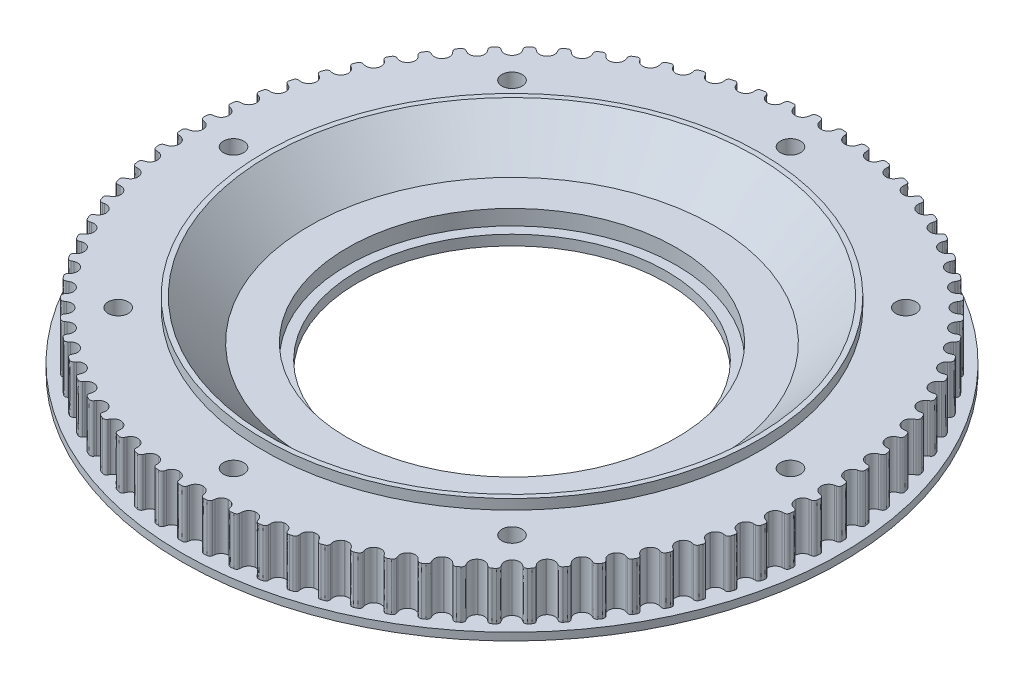
SolidWorks part; units mm, degrees
material "ABS"
ref_plane "Front Plane" through (0, 0, 0) normal (0, 0, 1) x (1, 0, 0)
ref_plane "Top Plane" through (0, 0, 0) normal (0, 1, 0) x (1, 0, 0)
ref_plane "Right Plane" through (0, 0, 0) normal (1, 0, 0) x (0, 0, -1)
sketch "Sketch1" plane through (0, 0, 0) normal (0, 0, 1) x (1, 0, 0)
  line L0 (32.5, 5) -> (40, 5)
  line L1 (30.5, 2) -> (30.5, 0)
  line L3 (63.09, 11) -> (49, 11)
  line L4 (32.5, 2) -> (32.5, 5)
  line L5 (30.5, 0) -> (65.09, 0)
  line L7 (48, 13) -> (40, 5)
  line L8 (32.5, 2) -> (30.5, 2)
  line L9 (48, 13) -> (49, 13)
  line L11 (65.09, 1.5) -> (65.09, 0)
  line L13 (63.09, 11) -> (63.09, 1.5)
  line L14 (63.09, 1.5) -> (65.09, 1.5)
  line L16 (49, 13) -> (49, 11)
  line L20 (0, 0) -> (0, 13) construction
revolve "Revolve1" add sketch "Sketch1" angle 360 about L20
sketch "Sketch2" plane through (0, 11, 0) normal (0, 1, 0) x (1, 0, 0)
  line L0 (52.0229, -31.9105) -> (52.0504, -31.8656)
  line L1 (48.2439, -39.2786) -> (48.5815, -39.4619)
  line L2 (53.7945, -31.248) -> (54.1566, -31.3763)
  line L3 (51.1769, -35.3724) -> (51.5279, -35.5286)
  line L4 (49.7127, -38.027) -> (49.4557, -37.7415)
  line L5 (45.0134, -42.9427) -> (45.3356, -43.1519)
  line L6 (49.3588, -35.8938) -> (49.3898, -35.8513)
  line L7 (46.3905, -39.6558) -> (46.4247, -39.6158)
  line L8 (39.6158, -46.4247) -> (39.6558, -46.3905)
  line L9 (37.7415, -49.4557) -> (38.027, -49.7127)
  line L10 (43.1361, -43.1734) -> (43.1734, -43.1361)
  line L11 (43.1519, -45.3356) -> (42.9427, -45.0134)
  line L12 (35.8512, -49.3898) -> (35.8939, -49.3588)
  line L13 (35.5286, -51.5279) -> (35.3724, -51.1769)
  line L14 (31.8656, -52.0504) -> (31.9105, -52.0229)
  line L15 (20.6117, -58.6979) -> (20.8038, -59.0306)
  line L16 (27.0305, -56.4514) -> (26.931, -56.0803)
  line L17 (18.8343, -58.0511) -> (18.8844, -58.0348)
  line L18 (27.6836, -54.3901) -> (27.7306, -54.3661)
  line L19 (41.5054, -46.342) -> (41.8102, -46.5759)
  line L20 (33.7449, -52.2644) -> (34.0094, -52.543)
  line L21 (39.4619, -48.5815) -> (39.2786, -48.2439)
  line L22 (13.1053, -61.2018) -> (13.0952, -60.8177)
  line L23 (22.518, -58.3982) -> (22.448, -58.0204)
  line L24 (25.1535, -56.8998) -> (25.3711, -57.2164)
  line L25 (23.3308, -56.3944) -> (23.3795, -56.3743)
  line L26 (17.8667, -59.9849) -> (17.8266, -59.6028)
  line L27 (14.2216, -59.3499) -> (14.2728, -59.3376)
  line L28 (31.3763, -54.1566) -> (31.248, -53.7945)
  line L29 (15.9427, -60.1341) -> (16.1081, -60.4809)
  line L30 (6.3394, -61.8878) -> (6.4485, -62.2561)
  line L31 (29.5403, -54.7508) -> (29.782, -55.0494)
  line L32 (11.1755, -61.1996) -> (11.3132, -61.5583)
  line L33 (-0.0263, -61.03) -> (0.0263, -61.03)
  line L34 (-4.8146, -60.8398) -> (-4.7621, -60.8439)
  line L35 (-9.5732, -60.2745) -> (-9.5212, -60.2827)
  line L36 (3.3699, -62.4984) -> (3.42, -62.1175)
  line L37 (1.4642, -62.1944) -> (1.5441, -62.5701)
  line L38 (4.7621, -60.8439) -> (4.8147, -60.8398)
  line L39 (-3.42, -62.1175) -> (-3.3699, -62.4984)
  line L40 (-1.5441, -62.5701) -> (-1.4642, -62.1944)
  line L41 (-6.4485, -62.2561) -> (-6.3394, -61.8878)
  line L42 (-23.3795, -56.3743) -> (-23.3308, -56.3944)
  line L43 (-8.2832, -61.6577) -> (-8.263, -62.0413)
  line L44 (-14.2728, -59.3376) -> (-14.2216, -59.3499)
  line L45 (-11.3132, -61.5583) -> (-11.1755, -61.1996)
  line L46 (-16.1081, -60.4809) -> (-15.9427, -60.1341)
  line L47 (-17.8266, -59.6028) -> (-17.8667, -59.9849)
  line L48 (-22.448, -58.0204) -> (-22.518, -58.3982)
  line L49 (-25.3711, -57.2164) -> (-25.1535, -56.8998)
  line L50 (-26.931, -56.0803) -> (-27.0305, -56.4514)
  line L51 (52.543, -34.0094) -> (52.2644, -33.7449)
  line L52 (9.5212, -60.2827) -> (9.5732, -60.2745)
  line L53 (-27.7305, -54.3662) -> (-27.6836, -54.3901)
  line L54 (-38.027, -49.7127) -> (-37.7415, -49.4557)
  line L55 (-35.3724, -51.1769) -> (-35.5286, -51.5279)
  line L56 (-42.9427, -45.0134) -> (-43.1519, -45.3356)
  line L57 (-31.248, -53.7945) -> (-31.3763, -54.1566)
  line L58 (-34.0094, -52.543) -> (-33.7449, -52.2644)
  line L59 (-35.8938, -49.3588) -> (-35.8513, -49.3898)
  line L60 (-39.2786, -48.2439) -> (-39.4619, -48.5815)
  line L61 (-31.9105, -52.0229) -> (-31.8656, -52.0504)
  line L62 (-41.8102, -46.5759) -> (-41.5054, -46.342)
  line L63 (-39.6558, -46.3905) -> (-39.6158, -46.4247)
  line L64 (-43.1734, -43.1361) -> (-43.1361, -43.1734)
  line L65 (-29.782, -55.0494) -> (-29.5403, -54.7509)
  line L66 (-46.342, -41.5054) -> (-46.5759, -41.8102)
  line L67 (-48.5815, -39.4619) -> (-48.2439, -39.2786)
  line L68 (-45.3356, -43.1519) -> (-45.0134, -42.9427)
  line L69 (-51.5279, -35.5286) -> (-51.1769, -35.3724)
  line L70 (-49.4557, -37.7415) -> (-49.7127, -38.027)
  line L71 (-54.1566, -31.3763) -> (-53.7945, -31.248)
  line L72 (-46.4247, -39.6158) -> (-46.3905, -39.6558)
  line L73 (-18.8844, -58.0348) -> (-18.8343, -58.0511)
  line L74 (-52.0504, -31.8656) -> (-52.0229, -31.9105)
  line L75 (-52.2644, -33.7449) -> (-52.543, -34.0094)
  line L76 (-20.8038, -59.0306) -> (-20.6117, -58.6979)
  line L77 (-49.3898, -35.8512) -> (-49.3588, -35.8939)
  line L78 (8.263, -62.0413) -> (8.2832, -61.6577)
  line L79 (-59.3499, -14.2216) -> (-59.3376, -14.2728)
  line L80 (-58.0511, -18.8343) -> (-58.0348, -18.8844)
  line L81 (-61.2018, -13.1053) -> (-60.8177, -13.0952)
  line L82 (-59.9849, -17.8667) -> (-59.6028, -17.8266)
  line L83 (-62.1944, -1.4642) -> (-62.5701, -1.5441)
  line L84 (-62.0413, -8.263) -> (-61.6577, -8.2832)
  line L85 (-60.1341, -15.9427) -> (-60.4809, -16.1081)
  line L86 (-61.03, 0.0263) -> (-61.03, -0.0263)
  line L87 (-62.4984, -3.3699) -> (-62.1175, -3.42)
  line L88 (-62.5701, 1.5441) -> (-62.1944, 1.4642)
  line L89 (-60.2827, -9.5212) -> (-60.2745, -9.5732)
  line L90 (-61.1996, -11.1755) -> (-61.5583, -11.3132)
  line L91 (-60.8439, -4.7621) -> (-60.8398, -4.8147)
  line L92 (-61.8878, -6.3394) -> (-62.2561, -6.4485)
  line L93 (-13.0952, -60.8177) -> (-13.1053, -61.2018)
  line L94 (46.5759, -41.8102) -> (46.342, -41.5054)
  line L95 (-9.5212, 60.2827) -> (-9.5732, 60.2745)
  line L96 (39.6558, 46.3905) -> (39.6158, 46.4247)
  line L97 (-14.2216, 59.3499) -> (-14.2728, 59.3376)
  line L98 (-25.1535, 56.8998) -> (-25.3711, 57.2164)
  line L99 (55.0494, -29.782) -> (54.7509, -29.5403)
  line L100 (11.3132, 61.5583) -> (11.1755, 61.1996)
  line L101 (1.5441, 62.5701) -> (1.4642, 62.1944)
  line L102 (9.5732, 60.2745) -> (9.5212, 60.2827)
  line L103 (35.8938, 49.3588) -> (35.8513, 49.3898)
  line L104 (56.3944, 23.3308) -> (56.3743, 23.3795)
  line L105 (-27.6836, 54.3901) -> (-27.7306, 54.3661)
  line L106 (-31.8656, 52.0504) -> (-31.9105, 52.0229)
  line L107 (56.0803, -26.931) -> (56.4514, -27.0305)
  line L108 (51.5279, 35.5286) -> (51.1769, 35.3724)
  line L109 (-35.5286, 51.5279) -> (-35.3724, 51.1769)
  line L110 (-31.3763, 54.1566) -> (-31.248, 53.7945)
  line L111 (-23.3308, 56.3944) -> (-23.3795, 56.3743)
  line L112 (-29.5403, 54.7508) -> (-29.782, 55.0494)
  line L113 (48.5815, 39.4619) -> (48.2439, 39.2786)
  line L114 (-27.0305, 56.4514) -> (-26.931, 56.0803)
  line L115 (54.1566, 31.3763) -> (53.7945, 31.248)
  line L116 (35.3724, 51.1769) -> (35.5286, 51.5279)
  line L117 (38.027, 49.7127) -> (37.7415, 49.4557)
  line L118 (-37.7415, 49.4557) -> (-38.027, 49.7127)
  line L119 (-18.8343, 58.0511) -> (-18.8844, 58.0348)
  line L120 (14.2728, 59.3376) -> (14.2216, 59.3499)
  line L121 (13.0952, 60.8177) -> (13.1053, 61.2018)
  line L122 (49.3898, 35.8512) -> (49.3588, 35.8939)
  line L123 (29.782, 55.0494) -> (29.5403, 54.7509)
  line L124 (-43.1519, 45.3356) -> (-42.9427, 45.0134)
  line L125 (-56.3944, -23.3308) -> (-56.3743, -23.3795)
  line L126 (54.3901, 27.6836) -> (54.3661, 27.7306)
  line L127 (25.3711, 57.2164) -> (25.1535, 56.8998)
  line L128 (45.3356, 43.1519) -> (45.0134, 42.9427)
  line L129 (-45.0134, 42.9427) -> (-45.3356, 43.1519)
  line L130 (41.8102, 46.5759) -> (41.5054, 46.342)
  line L131 (31.9105, 52.0229) -> (31.8656, 52.0504)
  line L132 (-39.4619, 48.5815) -> (-39.2786, 48.2439)
  line L133 (56.4514, 27.0305) -> (56.0803, 26.931)
  line L134 (23.3795, 56.3743) -> (23.3308, 56.3944)
  line L135 (46.342, 41.5054) -> (46.5759, 41.8102)
  line L136 (31.248, 53.7945) -> (31.3763, 54.1566)
  line L137 (-33.7449, 52.2644) -> (-34.0094, 52.543)
  line L138 (52.0504, 31.8656) -> (52.0229, 31.9105)
  line L139 (-22.518, 58.3982) -> (-22.448, 58.0204)
  line L140 (26.931, 56.0803) -> (27.0305, 56.4514)
  line L141 (-56.8998, -25.1535) -> (-57.2164, -25.3711)
  line L142 (-41.5054, 46.342) -> (-41.8102, 46.5759)
  line L143 (-46.5759, 41.8102) -> (-46.342, 41.5054)
  line L144 (-46.3905, 39.6558) -> (-46.4247, 39.6158)
  line L145 (-49.3588, 35.8938) -> (-49.3898, 35.8513)
  line L146 (-39.6158, 46.4247) -> (-39.6558, 46.3905)
  line L147 (-20.6117, 58.6979) -> (-20.8038, 59.0306)
  line L148 (-52.0229, 31.9105) -> (-52.0504, 31.8656)
  line L149 (8.2832, 61.6577) -> (8.263, 62.0413)
  line L150 (-51.1769, 35.3724) -> (-51.5279, 35.5286)
  line L151 (-48.2439, 39.2786) -> (-48.5815, 39.4619)
  line L152 (49.4557, 37.7415) -> (49.7127, 38.027)
  line L153 (-56.0803, 26.931) -> (-56.4514, 27.0305)
  line L154 (-54.3662, 27.7305) -> (-54.3901, 27.6836)
  line L155 (16.1081, 60.4809) -> (15.9427, 60.1341)
  line L156 (-43.1361, 43.1734) -> (-43.1734, 43.1361)
  line L157 (-59.0306, 20.8038) -> (-58.6979, 20.6117)
  line L158 (-52.543, 34.0094) -> (-52.2644, 33.7449)
  line L159 (-58.0204, 22.448) -> (-58.3982, 22.518)
  line L160 (-60.4809, 16.1081) -> (-60.1341, 15.9427)
  line L161 (-59.6028, 17.8266) -> (-59.9849, 17.8667)
  line L162 (-53.7945, 31.248) -> (-54.1566, 31.3763)
  line L163 (62.5701, -1.5441) -> (62.1944, -1.4642)
  line L164 (-55.0494, 29.782) -> (-54.7509, 29.5403)
  line L165 (-17.8667, 59.9849) -> (-17.8266, 59.6028)
  line L166 (-35.8512, 49.3898) -> (-35.8939, 49.3588)
  line L167 (-15.9427, 60.1341) -> (-16.1081, 60.4809)
  line L168 (-58.0348, 18.8844) -> (-58.0511, 18.8343)
  line L169 (-11.1755, 61.1996) -> (-11.3132, 61.5583)
  line L170 (-57.2164, 25.3711) -> (-56.8998, 25.1535)
  line L171 (-59.3376, 14.2728) -> (-59.3499, 14.2216)
  line L172 (-60.8398, 4.8146) -> (-60.8439, 4.7621)
  line L173 (-62.1175, 3.42) -> (-62.4984, 3.3699)
  line L174 (62.2561, -6.4485) -> (61.8878, -6.3394)
  line L175 (-60.8177, 13.0952) -> (-61.2018, 13.1053)
  line L176 (-13.1053, 61.2018) -> (-13.0952, 60.8177)
  line L177 (-61.6577, 8.2832) -> (-62.0413, 8.263)
  line L178 (56.3743, -23.3795) -> (56.3944, -23.3308)
  line L179 (59.0306, -20.8038) -> (58.6979, -20.6117)
  line L180 (62.1175, -3.42) -> (62.4984, -3.3699)
  line L181 (62.4984, 3.3699) -> (62.1175, 3.42)
  line L182 (39.2786, 48.2439) -> (39.4619, 48.5815)
  line L183 (34.0094, 52.543) -> (33.7449, 52.2644)
  line L184 (58.0204, -22.448) -> (58.3982, -22.518)
  line L185 (60.4809, -16.1081) -> (60.1341, -15.9427)
  line L186 (60.8439, 4.7621) -> (60.8398, 4.8147)
  line L187 (62.1944, 1.4642) -> (62.5701, 1.5441)
  line L188 (52.2644, 33.7449) -> (52.543, 34.0094)
  line L189 (57.2164, -25.3711) -> (56.8998, -25.1535)
  line L190 (60.1341, 15.9427) -> (60.4809, 16.1081)
  line L191 (27.7305, 54.3662) -> (27.6836, 54.3901)
  line L192 (-58.3982, -22.518) -> (-58.0204, -22.448)
  line L193 (-49.7127, 38.027) -> (-49.4557, 37.7415)
  line L194 (59.3499, 14.2216) -> (59.3376, 14.2728)
  line L195 (22.448, 58.0204) -> (22.518, 58.3982)
  line L196 (-56.3743, 23.3795) -> (-56.3944, 23.3308)
  line L197 (58.3982, 22.518) -> (58.0204, 22.448)
  line L198 (60.8398, -4.8146) -> (60.8439, -4.7621)
  line L199 (61.2018, 13.1053) -> (60.8177, 13.0952)
  line L200 (61.03, -0.0263) -> (61.03, 0.0263)
  line L201 (-58.6979, -20.6117) -> (-59.0306, -20.8038)
  line L202 (-62.2561, 6.4485) -> (-61.8878, 6.3394)
  line L203 (62.0413, 8.263) -> (61.6577, 8.2832)
  line L204 (58.0348, -18.8844) -> (58.0511, -18.8343)
  line L205 (59.6028, -17.8266) -> (59.9849, -17.8667)
  line L206 (61.8878, 6.3394) -> (62.2561, 6.4485)
  line L207 (-60.2745, 9.5732) -> (-60.2827, 9.5212)
  line L208 (61.5583, -11.3132) -> (61.1996, -11.1755)
  line L209 (60.8177, -13.0952) -> (61.2018, -13.1053)
  line L210 (54.3662, -27.7305) -> (54.3901, -27.6836)
  line L211 (61.6577, -8.2832) -> (62.0413, -8.263)
  line L212 (-54.3901, -27.6836) -> (-54.3661, -27.7306)
  line L213 (0.0263, 61.03) -> (-0.0263, 61.03)
  line L214 (59.9849, 17.8667) -> (59.6028, 17.8266)
  line L215 (60.2745, -9.5732) -> (60.2827, -9.5212)
  line L216 (-8.263, 62.0413) -> (-8.2832, 61.6577)
  line L217 (59.3376, -14.2728) -> (59.3499, -14.2216)
  line L218 (61.1996, 11.1755) -> (61.5583, 11.3132)
  line L219 (58.6979, 20.6117) -> (59.0306, 20.8038)
  line L220 (60.2827, 9.5212) -> (60.2745, 9.5732)
  line L221 (-56.4514, -27.0305) -> (-56.0803, -26.931)
  line L222 (56.8998, 25.1535) -> (57.2164, 25.3711)
  line L223 (58.0511, 18.8343) -> (58.0348, 18.8844)
  line L224 (-54.7508, -29.5403) -> (-55.0494, -29.782)
  line L225 (-3.3699, 62.4984) -> (-3.42, 62.1175)
  line L226 (-1.4642, 62.1944) -> (-1.5441, 62.5701)
  line L227 (-4.7621, 60.8439) -> (-4.8147, 60.8398)
  line L228 (17.8266, 59.6028) -> (17.8667, 59.9849)
  line L229 (4.8146, 60.8398) -> (4.7621, 60.8439)
  line L230 (-6.3394, 61.8878) -> (-6.4485, 62.2561)
  line L231 (3.42, 62.1175) -> (3.3699, 62.4984)
  line L232 (18.8844, 58.0348) -> (18.8343, 58.0511)
  line L233 (42.9427, 45.0134) -> (43.1519, 45.3356)
  line L234 (-61.5583, 11.3132) -> (-61.1996, 11.1755)
  line L235 (43.1734, 43.1361) -> (43.1361, 43.1734)
  line L236 (6.4485, 62.2561) -> (6.3394, 61.8878)
  line L237 (46.4247, 39.6158) -> (46.3905, 39.6558)
  line L238 (54.7508, 29.5403) -> (55.0494, 29.782)
  line L239 (20.8038, 59.0306) -> (20.6117, 58.6979)
  arc A4 (11.9987, -61.9385) -> (12.6175, -61.8154) centre (0, 0) ccw
  arc A5 (-12.6175, -61.8154) -> (-11.9987, -61.9385) centre (0, 0) ccw
  arc A6 (52.0229, -31.9105) -> (52.2644, -33.7449) centre (53.2762, -32.6786) ccw
  arc A7 (53.7945, -31.248) -> (52.0504, -31.8656) centre (53.3038, -32.6337) ccw
  arc A8 (49.3588, -35.8938) -> (49.4557, -37.7415) centre (50.5481, -36.7579) ccw
  arc A9 (46.3905, -39.6558) -> (46.342, -41.5054) centre (47.5083, -40.6105) ccw
  arc A10 (51.1769, -35.3724) -> (49.3898, -35.8513) centre (50.579, -36.7153) ccw
  arc A11 (41.5054, -46.342) -> (39.6558, -46.3905) centre (40.6105, -47.5083) ccw
  arc A12 (35.8512, -49.3898) -> (35.3724, -51.1769) centre (36.7153, -50.579) ccw
  arc A13 (43.1361, -43.1734) -> (42.9427, -45.0134) centre (44.1755, -44.2128) ccw
  arc A14 (45.0134, -42.9427) -> (43.1734, -43.1361) centre (44.2128, -44.1755) ccw
  arc A15 (39.6158, -46.4247) -> (39.2786, -48.2439) centre (40.5705, -47.5425) ccw
  arc A16 (48.2439, -39.2786) -> (46.4247, -39.6158) centre (47.5425, -40.5705) ccw
  arc A17 (33.7449, -52.2644) -> (31.9105, -52.0229) centre (32.6786, -53.2762) ccw
  arc A18 (16.8214, -60.8062) -> (17.4286, -60.6349) centre (0, 0) ccw
  arc A19 (31.8656, -52.0504) -> (31.248, -53.7945) centre (32.6337, -53.3038) ccw
  arc A20 (27.6836, -54.3901) -> (26.931, -56.0803) centre (28.3509, -55.6999) ccw
  arc A21 (37.7415, -49.4557) -> (35.8939, -49.3588) centre (36.7579, -50.5481) ccw
  arc A22 (18.8343, -58.0511) -> (17.8266, -59.6028) centre (19.2885, -59.4492) ccw
  arc A23 (15.9427, -60.1341) -> (14.2728, -59.3376) centre (14.6159, -60.767) ccw
  arc A24 (20.6117, -58.6979) -> (18.8844, -58.0348) centre (19.3386, -59.4329) ccw
  arc A25 (29.5403, -54.7508) -> (27.7306, -54.3661) centre (28.3979, -55.676) ccw
  arc A26 (-8.2832, -61.6577) -> (-9.5212, -60.2827) centre (-9.7511, -61.7346) ccw
  arc A27 (4.7621, -60.8439) -> (3.42, -62.1175) centre (4.8774, -62.3094) ccw
  arc A28 (14.2216, -59.3499) -> (13.0952, -60.8177) centre (14.5647, -60.7793) ccw
  arc A29 (23.3308, -56.3944) -> (22.448, -58.0204) centre (23.8934, -57.7526) ccw
  arc A30 (25.1535, -56.8998) -> (23.3795, -56.3743) centre (23.942, -57.7324) ccw
  arc A31 (1.4642, -62.1944) -> (0.0263, -61.03) centre (0.0263, -62.5) ccw
  arc A32 (6.3394, -61.8878) -> (4.8147, -60.8398) centre (4.93, -62.3053) ccw
  arc A33 (-4.8146, -60.8398) -> (-6.3394, -61.8878) centre (-4.93, -62.3053) ccw
  arc A34 (-0.0263, -61.03) -> (-1.4642, -62.1944) centre (-0.0263, -62.5) ccw
  arc A35 (-9.5732, -60.2745) -> (-11.1755, -61.1996) centre (-9.8032, -61.7264) ccw
  arc A36 (-14.2728, -59.3376) -> (-15.9427, -60.1341) centre (-14.6159, -60.767) ccw
  arc A37 (-27.7305, -54.3662) -> (-29.5403, -54.7509) centre (-28.3979, -55.676) ccw
  arc A38 (-22.448, -58.0204) -> (-23.3308, -56.3944) centre (-23.8934, -57.7526) ccw
  arc A39 (-13.0952, -60.8177) -> (-14.2216, -59.3499) centre (-14.5647, -60.7793) ccw
  arc A40 (-17.8266, -59.6028) -> (-18.8343, -58.0511) centre (-19.2885, -59.4492) ccw
  arc A41 (7.1021, -62.689) -> (7.7286, -62.6148) centre (0, 0) ccw
  arc A42 (11.1755, -61.1996) -> (9.5732, -60.2745) centre (9.8032, -61.7264) ccw
  arc A43 (-3.42, -62.1175) -> (-4.7621, -60.8439) centre (-4.8774, -62.3094) ccw
  arc A44 (-26.931, -56.0803) -> (-27.6836, -54.3901) centre (-28.3509, -55.6999) ccw
  arc A45 (-23.3795, -56.3743) -> (-25.1535, -56.8998) centre (-23.942, -57.7324) ccw
  arc A46 (-31.9105, -52.0229) -> (-33.7449, -52.2644) centre (-32.6786, -53.2762) ccw
  arc A47 (-31.248, -53.7945) -> (-31.8656, -52.0504) centre (-32.6337, -53.3038) ccw
  arc A48 (-35.8938, -49.3588) -> (-37.7415, -49.4557) centre (-36.7579, -50.5481) ccw
  arc A49 (-39.2786, -48.2439) -> (-39.6158, -46.4247) centre (-40.5705, -47.5425) ccw
  arc A50 (-35.3724, -51.1769) -> (-35.8513, -49.3898) centre (-36.7153, -50.579) ccw
  arc A51 (-39.6558, -46.3905) -> (-41.5054, -46.342) centre (-40.6105, -47.5083) ccw
  arc A52 (-42.9427, -45.0134) -> (-43.1361, -43.1734) centre (-44.1755, -44.2128) ccw
  arc A53 (-43.1734, -43.1361) -> (-45.0134, -42.9427) centre (-44.2128, -44.1755) ccw
  arc A54 (-46.4247, -39.6158) -> (-48.2439, -39.2786) centre (-47.5425, -40.5705) ccw
  arc A55 (9.5212, -60.2827) -> (8.2832, -61.6577) centre (9.7511, -61.7346) ccw
  arc A56 (-46.342, -41.5054) -> (-46.3905, -39.6558) centre (-47.5083, -40.6105) ccw
  arc A57 (-49.4557, -37.7415) -> (-49.3588, -35.8939) centre (-50.5481, -36.7579) ccw
  arc A58 (-52.0504, -31.8656) -> (-53.7945, -31.248) centre (-53.3038, -32.6337) ccw
  arc A59 (-49.3898, -35.8512) -> (-51.1769, -35.3724) centre (-50.579, -36.7153) ccw
  arc A60 (-52.2644, -33.7449) -> (-52.0229, -31.9105) centre (-53.2762, -32.6786) ccw
  arc A61 (-58.0511, -18.8343) -> (-59.6028, -17.8266) centre (-59.4492, -19.2885) ccw
  arc A62 (-58.6979, -20.6117) -> (-58.0348, -18.8844) centre (-59.4329, -19.3386) ccw
  arc A63 (-60.8439, -4.7621) -> (-62.1175, -3.42) centre (-62.3094, -4.8774) ccw
  arc A64 (-59.3499, -14.2216) -> (-60.8177, -13.0952) centre (-60.7793, -14.5647) ccw
  arc A65 (-60.2827, -9.5212) -> (-61.6577, -8.2832) centre (-61.7346, -9.7511) ccw
  arc A66 (-61.03, 0.0263) -> (-62.1944, 1.4642) centre (-62.5, 0.0263) ccw
  arc A67 (-61.8878, -6.3394) -> (-60.8398, -4.8147) centre (-62.3053, -4.93) ccw
  arc A68 (42.5934, -46.542) -> (43.0567, -46.1137) centre (0, 0) ccw
  arc A69 (-62.1944, -1.4642) -> (-61.03, -0.0263) centre (-62.5, -0.0263) ccw
  arc A70 (46.1137, -43.0567) -> (46.542, -42.5934) centre (0, 0) ccw
  arc A71 (21.5403, -59.2989) -> (22.1322, -59.0806) centre (0, 0) ccw
  arc A72 (-2.7921, -63.0282) -> (-2.1617, -63.053) centre (0, 0) ccw
  arc A73 (-61.1996, -11.1755) -> (-60.2745, -9.5732) centre (-61.7264, -9.8032) ccw
  arc A74 (-35.3128, -52.2815) -> (-34.7882, -52.632) centre (0, 0) ccw
  arc A75 (30.5515, -55.1992) -> (31.102, -54.8909) centre (0, 0) ccw
  arc A76 (-55.1992, -30.5515) -> (-54.8909, -31.102) centre (0, 0) ccw
  arc A77 (-46.542, -42.5934) -> (-46.1137, -43.0567) centre (0, 0) ccw
  arc A78 (2.1617, -63.053) -> (2.7921, -63.0282) centre (0, 0) ccw
  arc A79 (-31.102, -54.8909) -> (-30.5515, -55.1992) centre (0, 0) ccw
  arc A80 (-60.1341, -15.9427) -> (-59.3376, -14.2728) centre (-60.767, -14.6159) ccw
  arc A81 (-43.0567, -46.1137) -> (-42.5934, -46.542) centre (0, 0) ccw
  arc A82 (49.3497, -39.3059) -> (49.7403, -38.8104) centre (0, 0) ccw
  arc A83 (-18.8844, -58.0348) -> (-20.6117, -58.6979) centre (-19.3386, -59.4329) ccw
  arc A84 (34.7882, -52.632) -> (35.3128, -52.2815) centre (0, 0) ccw
  arc A85 (-26.6994, -57.162) -> (-26.1264, -57.4261) centre (0, 0) ccw
  arc A86 (26.1264, -57.4261) -> (26.6994, -57.162) centre (0, 0) ccw
  arc A87 (52.2815, -35.3128) -> (52.632, -34.7882) centre (0, 0) ccw
  arc A88 (-39.3059, -49.3497) -> (-38.8104, -49.7403) centre (0, 0) ccw
  arc A89 (-22.1322, -59.0806) -> (-21.5403, -59.2989) centre (0, 0) ccw
  arc A90 (-52.632, -34.7882) -> (-52.2815, -35.3128) centre (0, 0) ccw
  arc A91 (-49.7403, -38.8104) -> (-49.3497, -39.3059) centre (0, 0) ccw
  arc A92 (-17.4286, -60.6349) -> (-16.8214, -60.8062) centre (0, 0) ccw
  arc A93 (-7.7286, -62.6148) -> (-7.1021, -62.689) centre (0, 0) ccw
  arc A94 (54.8909, -31.102) -> (55.1992, -30.5515) centre (0, 0) ccw
  arc A95 (38.8104, -49.7403) -> (39.3059, -49.3497) centre (0, 0) ccw
  arc A96 (54.3901, 27.6836) -> (56.0803, 26.931) centre (55.6999, 28.3509) ccw
  arc A97 (-15.9427, 60.1341) -> (-14.2728, 59.3376) centre (-14.6159, 60.767) ccw
  arc A98 (3.42, 62.1175) -> (4.7621, 60.8439) centre (4.8774, 62.3094) ccw
  arc A99 (-25.1535, 56.8998) -> (-23.3795, 56.3743) centre (-23.942, 57.7324) ccw
  arc A100 (-23.3308, 56.3944) -> (-22.448, 58.0204) centre (-23.8934, 57.7526) ccw
  arc A101 (-20.6117, 58.6979) -> (-18.8844, 58.0348) centre (-19.3386, 59.4329) ccw
  arc A102 (17.8266, 59.6028) -> (18.8343, 58.0511) centre (19.2885, 59.4492) ccw
  arc A103 (-27.6836, 54.3901) -> (-26.931, 56.0803) centre (-28.3509, 55.6999) ccw
  arc A104 (-31.8656, 52.0504) -> (-31.248, 53.7945) centre (-32.6337, 53.3038) ccw
  arc A105 (35.3724, 51.1769) -> (35.8513, 49.3898) centre (36.7153, 50.579) ccw
  arc A106 (9.5732, 60.2745) -> (11.1755, 61.1996) centre (9.8032, 61.7264) ccw
  arc A107 (8.2832, 61.6577) -> (9.5212, 60.2827) centre (9.7511, 61.7346) ccw
  arc A108 (14.2728, 59.3376) -> (15.9427, 60.1341) centre (14.6159, 60.767) ccw
  arc A109 (46.342, 41.5054) -> (46.3905, 39.6558) centre (47.5083, 40.6105) ccw
  arc A110 (62.1175, -3.42) -> (60.8439, -4.7621) centre (62.3094, -4.8774) ccw
  arc A111 (-39.6158, 46.4247) -> (-39.2786, 48.2439) centre (-40.5705, 47.5425) ccw
  arc A112 (-33.7449, 52.2644) -> (-31.9105, 52.0229) centre (-32.6786, 53.2762) ccw
  arc A113 (13.0952, 60.8177) -> (14.2216, 59.3499) centre (14.5647, 60.7793) ccw
  arc A114 (46.4247, 39.6158) -> (48.2439, 39.2786) centre (47.5425, 40.5705) ccw
  arc A115 (27.7305, 54.3662) -> (29.5403, 54.7509) centre (28.3979, 55.676) ccw
  arc A116 (-29.5403, 54.7508) -> (-27.7306, 54.3661) centre (-28.3979, 55.676) ccw
  arc A117 (-52.0229, 31.9105) -> (-52.2644, 33.7449) centre (-53.2762, 32.6786) ccw
  arc A118 (49.4557, 37.7415) -> (49.3588, 35.8939) centre (50.5481, 36.7579) ccw
  arc A119 (56.8998, 25.1535) -> (56.3743, 23.3795) centre (57.7324, 23.942) ccw
  arc A120 (-37.7415, 49.4557) -> (-35.8939, 49.3588) centre (-36.7579, 50.5481) ccw
  arc A121 (-43.1361, 43.1734) -> (-42.9427, 45.0134) centre (-44.1755, 44.2128) ccw
  arc A122 (-41.5054, 46.342) -> (-39.6558, 46.3905) centre (-40.6105, 47.5083) ccw
  arc A123 (-35.8512, 49.3898) -> (-35.3724, 51.1769) centre (-36.7153, 50.579) ccw
  arc A124 (23.3795, 56.3743) -> (25.1535, 56.8998) centre (23.942, 57.7324) ccw
  arc A125 (-45.0134, 42.9427) -> (-43.1734, 43.1361) centre (-44.2128, 44.1755) ccw
  arc A126 (43.1734, 43.1361) -> (45.0134, 42.9427) centre (44.2128, 44.1755) ccw
  arc A127 (-57.4261, -26.1264) -> (-57.162, -26.6994) centre (0, 0) ccw
  arc A128 (-49.3588, 35.8938) -> (-49.4557, 37.7415) centre (-50.5481, 36.7579) ccw
  arc A129 (-51.1769, 35.3724) -> (-49.3898, 35.8513) centre (-50.579, 36.7153) ccw
  arc A130 (-38.8104, 49.7403) -> (-39.3059, 49.3497) centre (0, 0) ccw
  arc A131 (-48.2439, 39.2786) -> (-46.4247, 39.6158) centre (-47.5425, 40.5705) ccw
  arc A132 (31.248, 53.7945) -> (31.8656, 52.0504) centre (32.6337, 53.3038) ccw
  arc A133 (-54.3662, 27.7305) -> (-54.7509, 29.5403) centre (-55.676, 28.3979) ccw
  arc A134 (-58.0204, 22.448) -> (-56.3944, 23.3308) centre (-57.7526, 23.8934) ccw
  arc A135 (61.03, -0.0263) -> (62.1944, -1.4642) centre (62.5, -0.0263) ccw
  arc A136 (-59.3376, 14.2728) -> (-60.1341, 15.9427) centre (-60.767, 14.6159) ccw
  arc A137 (4.8146, 60.8398) -> (6.3394, 61.8878) centre (4.93, 62.3053) ccw
  arc A138 (-56.3743, 23.3795) -> (-56.8998, 25.1535) centre (-57.7324, 23.942) ccw
  arc A139 (-53.7945, 31.248) -> (-52.0504, 31.8656) centre (-53.3038, 32.6337) ccw
  arc A140 (-18.8343, 58.0511) -> (-17.8266, 59.6028) centre (-19.2885, 59.4492) ccw
  arc A141 (56.3743, -23.3795) -> (56.8998, -25.1535) centre (57.7324, -23.942) ccw
  arc A142 (62.1944, 1.4642) -> (61.03, 0.0263) centre (62.5, 0.0263) ccw
  arc A143 (-60.8177, 13.0952) -> (-59.3499, 14.2216) centre (-60.7793, 14.5647) ccw
  arc A144 (-62.1175, 3.42) -> (-60.8439, 4.7621) centre (-62.3094, 4.8774) ccw
  arc A145 (26.931, 56.0803) -> (27.6836, 54.3901) centre (28.3509, 55.6999) ccw
  arc A146 (-60.8062, -16.8214) -> (-60.6349, -17.4286) centre (0, 0) ccw
  arc A147 (7.7286, 62.6148) -> (7.1021, 62.689) centre (0, 0) ccw
  arc A148 (49.3898, 35.8512) -> (51.1769, 35.3724) centre (50.579, 36.7153) ccw
  arc A149 (-30.5515, 55.1992) -> (-31.102, 54.8909) centre (0, 0) ccw
  arc A150 (60.8439, 4.7621) -> (62.1175, 3.42) centre (62.3094, 4.8774) ccw
  arc A151 (58.0511, 18.8343) -> (59.6028, 17.8266) centre (59.4492, 19.2885) ccw
  arc A152 (31.9105, 52.0229) -> (33.7449, 52.2644) centre (32.6786, 53.2762) ccw
  arc A153 (35.3128, 52.2815) -> (34.7882, 52.632) centre (0, 0) ccw
  arc A154 (60.1341, 15.9427) -> (59.3376, 14.2728) centre (60.767, 14.6159) ccw
  arc A155 (60.8062, 16.8214) -> (60.6349, 17.4286) centre (0, 0) ccw
  arc A156 (-61.6577, 8.2832) -> (-60.2827, 9.5212) centre (-61.7346, 9.7511) ccw
  arc A157 (-59.6028, 17.8266) -> (-58.0511, 18.8343) centre (-59.4492, 19.2885) ccw
  arc A158 (-46.3905, 39.6558) -> (-46.342, 41.5054) centre (-47.5083, 40.6105) ccw
  arc A159 (54.7508, 29.5403) -> (54.3661, 27.7306) centre (55.676, 28.3979) ccw
  arc A160 (-60.8398, 4.8146) -> (-61.8878, 6.3394) centre (-62.3053, 4.93) ccw
  arc A161 (56.0803, -26.931) -> (54.3901, -27.6836) centre (55.6999, -28.3509) ccw
  arc A162 (58.0204, -22.448) -> (56.3944, -23.3308) centre (57.7526, -23.8934) ccw
  arc A163 (59.6028, -17.8266) -> (58.0511, -18.8343) centre (59.4492, -19.2885) ccw
  arc A164 (-58.0348, 18.8844) -> (-58.6979, 20.6117) centre (-59.4329, 19.3386) ccw
  arc A165 (-56.0803, 26.931) -> (-54.3901, 27.6836) centre (-55.6999, 28.3509) ccw
  arc A166 (-60.2745, 9.5732) -> (-61.1996, 11.1755) centre (-61.7264, 9.8032) ccw
  arc A167 (61.8878, 6.3394) -> (60.8398, 4.8147) centre (62.3053, 4.93) ccw
  arc A168 (58.6979, 20.6117) -> (58.0348, 18.8844) centre (59.4329, 19.3386) ccw
  arc A169 (60.2827, 9.5212) -> (61.6577, 8.2832) centre (61.7346, 9.7511) ccw
  arc A170 (59.3376, -14.2728) -> (60.1341, -15.9427) centre (60.767, -14.6159) ccw
  arc A171 (-54.7508, -29.5403) -> (-54.3661, -27.7306) centre (-55.676, -28.3979) ccw
  arc A172 (-26.1264, 57.4261) -> (-26.6994, 57.162) centre (0, 0) ccw
  arc A173 (58.0348, -18.8844) -> (58.6979, -20.6117) centre (59.4329, -19.3386) ccw
  arc A174 (61.1996, 11.1755) -> (60.2745, 9.5732) centre (61.7264, 9.8032) ccw
  arc A175 (60.8177, -13.0952) -> (59.3499, -14.2216) centre (60.7793, -14.5647) ccw
  arc A176 (60.2745, -9.5732) -> (61.1996, -11.1755) centre (61.7264, -9.8032) ccw
  arc A177 (56.3944, 23.3308) -> (58.0204, 22.448) centre (57.7526, 23.8934) ccw
  arc A178 (-54.3901, -27.6836) -> (-56.0803, -26.931) centre (-55.6999, -28.3509) ccw
  arc A179 (2.7921, 63.0282) -> (2.1617, 63.053) centre (0, 0) ccw
  arc A180 (59.3499, 14.2216) -> (60.8177, 13.0952) centre (60.7793, 14.5647) ccw
  arc A181 (-56.3944, -23.3308) -> (-58.0204, -22.448) centre (-57.7526, -23.8934) ccw
  arc A182 (60.8398, -4.8146) -> (61.8878, -6.3394) centre (62.3053, -4.93) ccw
  arc A183 (54.3662, -27.7305) -> (54.7509, -29.5403) centre (55.676, -28.3979) ccw
  arc A184 (61.6577, -8.2832) -> (60.2827, -9.5212) centre (61.7346, -9.7511) ccw
  arc A185 (0.0263, 61.03) -> (1.4642, 62.1944) centre (0.0263, 62.5) ccw
  arc A186 (-60.6349, 17.4286) -> (-60.8062, 16.8214) centre (0, 0) ccw
  arc A187 (39.3059, 49.3497) -> (38.8104, 49.7403) centre (0, 0) ccw
  arc A188 (-1.4642, 62.1944) -> (-0.0263, 61.03) centre (-0.0263, 62.5) ccw
  arc A189 (-9.5212, 60.2827) -> (-8.2832, 61.6577) centre (-9.7511, 61.7346) ccw
  arc A190 (63.0282, -2.7921) -> (63.053, -2.1617) centre (0, 0) ccw
  arc A191 (57.4261, 26.1264) -> (57.162, 26.6994) centre (0, 0) ccw
  arc A192 (52.0504, 31.8656) -> (53.7945, 31.248) centre (53.3038, 32.6337) ccw
  arc A193 (35.8938, 49.3588) -> (37.7415, 49.4557) centre (36.7579, 50.5481) ccw
  arc A194 (-4.7621, 60.8439) -> (-3.42, 62.1175) centre (-4.8774, 62.3094) ccw
  arc A195 (-6.3394, 61.8878) -> (-4.8147, 60.8398) centre (-4.93, 62.3053) ccw
  arc A196 (39.2786, 48.2439) -> (39.6158, 46.4247) centre (40.5705, 47.5425) ccw
  arc A197 (-11.1755, 61.1996) -> (-9.5732, 60.2745) centre (-9.8032, 61.7264) ccw
  arc A198 (18.8844, 58.0348) -> (20.6117, 58.6979) centre (19.3386, 59.4329) ccw
  arc A199 (22.448, 58.0204) -> (23.3308, 56.3944) centre (23.8934, 57.7526) ccw
  arc A200 (-42.5934, 46.542) -> (-43.0567, 46.1137) centre (0, 0) ccw
  arc A201 (62.689, 7.1021) -> (62.6148, 7.7286) centre (0, 0) ccw
  arc A202 (61.9385, 11.9987) -> (61.8154, 12.6175) centre (0, 0) ccw
  arc A203 (59.2989, 21.5403) -> (59.0806, 22.1322) centre (0, 0) ccw
  arc A204 (26.6994, 57.162) -> (26.1264, 57.4261) centre (0, 0) ccw
  arc A205 (39.6558, 46.3905) -> (41.5054, 46.342) centre (40.6105, 47.5083) ccw
  arc A206 (-56.8998, -25.1535) -> (-56.3743, -23.3795) centre (-57.7324, -23.942) ccw
  arc A207 (62.6148, -7.7286) -> (62.689, -7.1021) centre (0, 0) ccw
  arc A208 (55.1992, 30.5515) -> (54.8909, 31.102) centre (0, 0) ccw
  arc A209 (-54.8909, 31.102) -> (-55.1992, 30.5515) centre (0, 0) ccw
  arc A210 (52.2644, 33.7449) -> (52.0229, 31.9105) centre (53.2762, 32.6786) ccw
  arc A211 (-61.9385, -11.9987) -> (-61.8154, -12.6175) centre (0, 0) ccw
  arc A212 (31.102, 54.8909) -> (30.5515, 55.1992) centre (0, 0) ccw
  arc A213 (-7.1021, 62.689) -> (-7.7286, 62.6148) centre (0, 0) ccw
  arc A214 (57.162, -26.6994) -> (57.4261, -26.1264) centre (0, 0) ccw
  arc A215 (-34.7882, 52.632) -> (-35.3128, 52.2815) centre (0, 0) ccw
  arc A216 (43.0567, 46.1137) -> (42.5934, 46.542) centre (0, 0) ccw
  arc A217 (59.0806, -22.1322) -> (59.2989, -21.5403) centre (0, 0) ccw
  arc A218 (-63.0282, 2.7921) -> (-63.053, 2.1617) centre (0, 0) ccw
  arc A219 (-59.0806, 22.1322) -> (-59.2989, 21.5403) centre (0, 0) ccw
  arc A220 (-16.8214, 60.8062) -> (-17.4286, 60.6349) centre (0, 0) ccw
  arc A221 (12.6175, 61.8154) -> (11.9987, 61.9385) centre (0, 0) ccw
  arc A222 (-11.9987, 61.9385) -> (-12.6175, 61.8154) centre (0, 0) ccw
  arc A223 (46.542, 42.5934) -> (46.1137, 43.0567) centre (0, 0) ccw
  arc A224 (63.053, 2.1617) -> (63.0282, 2.7921) centre (0, 0) ccw
  arc A225 (-21.5403, 59.2989) -> (-22.1322, 59.0806) centre (0, 0) ccw
  arc A226 (-14.2216, 59.3499) -> (-13.0952, 60.8177) centre (-14.5647, 60.7793) ccw
  arc A227 (61.8154, -12.6175) -> (61.9385, -11.9987) centre (0, 0) ccw
  arc A228 (22.1322, 59.0806) -> (21.5403, 59.2989) centre (0, 0) ccw
  arc A229 (42.9427, 45.0134) -> (43.1361, 43.1734) centre (44.1755, 44.2128) ccw
  arc A230 (17.4286, 60.6349) -> (16.8214, 60.8062) centre (0, 0) ccw
  arc A231 (-57.162, 26.6994) -> (-57.4261, 26.1264) centre (0, 0) ccw
  arc A232 (-49.3497, 39.3059) -> (-49.7403, 38.8104) centre (0, 0) ccw
  arc A233 (-2.1617, 63.053) -> (-2.7921, 63.0282) centre (0, 0) ccw
  arc A234 (49.7403, 38.8104) -> (49.3497, 39.3059) centre (0, 0) ccw
  arc A235 (-63.053, -2.1617) -> (-63.0282, -2.7921) centre (0, 0) ccw
  arc A236 (-61.8154, 12.6175) -> (-61.9385, 11.9987) centre (0, 0) ccw
  arc A237 (-59.2989, -21.5403) -> (-59.0806, -22.1322) centre (0, 0) ccw
  arc A238 (-62.689, -7.1021) -> (-62.6148, -7.7286) centre (0, 0) ccw
  arc A239 (52.632, 34.7882) -> (52.2815, 35.3128) centre (0, 0) ccw
  arc A240 (-62.6148, 7.7286) -> (-62.689, 7.1021) centre (0, 0) ccw
  arc A241 (60.6349, -17.4286) -> (60.8062, -16.8214) centre (0, 0) ccw
  arc A242 (-52.2815, 35.3128) -> (-52.632, 34.7882) centre (0, 0) ccw
  arc A243 (-46.1137, 43.0567) -> (-46.542, 42.5934) centre (0, 0) ccw
  circle A244 centre (0, 0) radius 63.09
  spline S0 degree 3 poles (11.9987, -61.9385) (11.9148, -61.9548) (11.8299, -61.9524) (11.6765, -61.9191) (11.6081, -61.8887) (11.4336, -61.7752) (11.3568, -61.6716) (11.3132, -61.5583) knots 0 0 0 0 0.25 0.25 0.5 0.5 1 1 1 1
  spline S1 degree 3 poles (38.8104, -49.7403) (38.7431, -49.7929) (38.6664, -49.8293) (38.5146, -49.8693) (38.4398, -49.8733) (38.2328, -49.8513) (38.1173, -49.7939) (38.027, -49.7127) knots 0 0 0 0 0.25 0.25 0.5 0.5 1 1 1 1
  spline S2 degree 3 poles (-20.8038, -59.0306) (-20.8343, -59.0834) (-20.8721, -59.1312) (-20.9648, -59.2168) (-21.0196, -59.254) (-21.1459, -59.3106) (-21.2177, -59.33) (-21.3758, -59.3391) (-21.4601, -59.3281) (-21.5403, -59.2989) knots 0 0 0 0 0.25 0.25 0.5 0.5 0.75 0.75 1 1 1 1
  spline S3 degree 3 poles (-11.3132, -61.5583) (-11.3351, -61.6152) (-11.365, -61.6683) (-11.4432, -61.7673) (-11.4914, -61.8127) (-11.6073, -61.8883) (-11.6753, -61.9187) (-11.83, -61.9525) (-11.9149, -61.9547) (-11.9987, -61.9385) knots 0 0 0 0 0.25 0.25 0.5 0.5 0.75 0.75 1 1 1 1
  spline S4 degree 3 poles (13.1053, -61.2018) (13.1068, -61.2628) (13.0996, -61.3233) (13.0652, -61.4447) (13.038, -61.5051) (12.9599, -61.6193) (12.9087, -61.6734) (12.7787, -61.7638) (12.7011, -61.7984) (12.6175, -61.8154) knots 0 0 0 0 0.25 0.25 0.5 0.5 0.75 0.75 1 1 1 1
  spline S5 degree 3 poles (35.5286, -51.5279) (35.5534, -51.5836) (35.5699, -51.6423) (35.5845, -51.7676) (35.5825, -51.8338) (35.5541, -51.9693) (35.5275, -52.0388) (35.442, -52.1721) (35.3835, -52.2337) (35.3128, -52.2815) knots 0 0 0 0 0.25 0.25 0.5 0.5 0.75 0.75 1 1 1 1
  spline S6 degree 3 poles (49.7127, -38.027) (49.7535, -38.0724) (49.7873, -38.1231) (49.84, -38.2377) (49.8585, -38.3013) (49.8733, -38.4389) (49.8695, -38.5133) (49.8294, -38.6664) (49.7928, -38.7431) (49.7403, -38.8104) knots 0 0 0 0 0.25 0.25 0.5 0.5 0.75 0.75 1 1 1 1
  spline S7 degree 3 poles (46.5759, -41.8102) (46.613, -41.8586) (46.6427, -41.9118) (46.6863, -42.0302) (46.6998, -42.0951) (46.7037, -42.2334) (46.6941, -42.3073) (46.642, -42.4568) (46.5996, -42.5304) (46.542, -42.5934) knots 0 0 0 0 0.25 0.25 0.5 0.5 0.75 0.75 1 1 1 1
  spline S8 degree 3 poles (46.1137, -43.0567) (46.0554, -43.1191) (45.9853, -43.1671) (45.8416, -43.2303) (45.7684, -43.246) (45.5605, -43.2567) (45.4375, -43.218) (45.3356, -43.1519) knots 0 0 0 0 0.25 0.25 0.5 0.5 1 1 1 1
  spline S9 degree 3 poles (43.1519, -45.3356) (43.1851, -45.3868) (43.2106, -45.4422) (43.2447, -45.5636) (43.2531, -45.6293) (43.2461, -45.7676) (43.2308, -45.8404) (43.1671, -45.9854) (43.119, -46.0554) (43.0567, -46.1137) knots 0 0 0 0 0.25 0.25 0.5 0.5 0.75 0.75 1 1 1 1
  spline S10 degree 3 poles (22.518, -58.3982) (22.5291, -58.4582) (22.5314, -58.5191) (22.5164, -58.6443) (22.499, -58.7082) (22.4397, -58.8333) (22.3977, -58.8947) (22.2834, -59.0043) (22.2121, -59.0506) (22.1322, -59.0806) knots 0 0 0 0 0.25 0.25 0.5 0.5 0.75 0.75 1 1 1 1
  spline S11 degree 3 poles (2.1617, -63.053) (2.0763, -63.0559) (1.9928, -63.0403) (1.8465, -62.9834) (1.7836, -62.9427) (1.6291, -62.8032) (1.5695, -62.6889) (1.5441, -62.5701) knots 0 0 0 0 0.25 0.25 0.5 0.5 1 1 1 1
  spline S12 degree 3 poles (3.3699, -62.4984) (3.3618, -62.5589) (3.3452, -62.6175) (3.2923, -62.732) (3.256, -62.7874) (3.1609, -62.888) (3.102, -62.9335) (2.9594, -63.0024) (2.8774, -63.0244) (2.7921, -63.0282) knots 0 0 0 0 0.25 0.25 0.5 0.5 0.75 0.75 1 1 1 1
  spline S13 degree 3 poles (21.5403, -59.2989) (21.46, -59.3281) (21.3758, -59.3391) (21.2191, -59.3302) (21.1467, -59.3109) (20.9566, -59.226) (20.8646, -59.1357) (20.8038, -59.0306) knots 0 0 0 0 0.25 0.25 0.5 0.5 1 1 1 1
  spline S14 degree 3 poles (-35.3128, -52.2815) (-35.3836, -52.2337) (-35.4419, -52.172) (-35.5269, -52.04) (-35.5538, -51.9701) (-35.5969, -51.7664) (-35.5779, -51.6389) (-35.5286, -51.5279) knots 0 0 0 0 0.25 0.25 0.5 0.5 1 1 1 1
  spline S15 degree 3 poles (-34.0094, -52.543) (-34.0514, -52.5872) (-34.0993, -52.6249) (-34.2094, -52.6865) (-34.2714, -52.7099) (-34.4074, -52.7354) (-34.4818, -52.7375) (-34.6377, -52.7095) (-34.717, -52.6791) (-34.7882, -52.632) knots 0 0 0 0 0.25 0.25 0.5 0.5 0.75 0.75 1 1 1 1
  spline S16 degree 3 poles (42.5934, -46.542) (42.5303, -46.5996) (42.4567, -46.642) (42.3085, -46.6937) (42.2343, -46.7036) (42.0262, -46.698) (41.9066, -46.6497) (41.8102, -46.5759) knots 0 0 0 0 0.25 0.25 0.5 0.5 1 1 1 1
  spline S17 degree 3 poles (31.3763, -54.1566) (31.3966, -54.2141) (31.4084, -54.2739) (31.4132, -54.4) (31.406, -54.4658) (31.367, -54.5986) (31.3351, -54.6659) (31.2393, -54.792) (31.1762, -54.8489) (31.102, -54.8909) knots 0 0 0 0 0.25 0.25 0.5 0.5 0.75 0.75 1 1 1 1
  spline S18 degree 3 poles (26.1264, -57.4261) (26.0487, -57.4615) (25.9656, -57.479) (25.8086, -57.4824) (25.735, -57.4689) (25.5388, -57.3992) (25.44, -57.3164) (25.3711, -57.2164) knots 0 0 0 0 0.25 0.25 0.5 0.5 1 1 1 1
  spline S19 degree 3 poles (30.5515, -55.1992) (30.4767, -55.2406) (30.3953, -55.2646) (30.2391, -55.2803) (30.1646, -55.2726) (29.9636, -55.2185) (29.8586, -55.1437) (29.782, -55.0494) knots 0 0 0 0 0.25 0.25 0.5 0.5 1 1 1 1
  spline S20 degree 3 poles (-31.102, -54.8909) (-31.1763, -54.8488) (-31.2393, -54.7919) (-31.3343, -54.667) (-31.3667, -54.5994) (-31.4256, -54.3998) (-31.4167, -54.2711) (-31.3763, -54.1566) knots 0 0 0 0 0.25 0.25 0.5 0.5 1 1 1 1
  spline S21 degree 3 poles (-2.7921, -63.0282) (-2.8774, -63.0244) (-2.9594, -63.0023) (-3.1008, -62.9341) (-3.1603, -62.8886) (-3.3034, -62.7375) (-3.3539, -62.6188) (-3.3699, -62.4984) knots 0 0 0 0 0.25 0.25 0.5 0.5 1 1 1 1
  spline S22 degree 3 poles (-46.542, -42.5934) (-46.5996, -42.5303) (-46.642, -42.4567) (-46.6937, -42.3085) (-46.7036, -42.2343) (-46.698, -42.0262) (-46.6497, -41.9066) (-46.5759, -41.8102) knots 0 0 0 0 0.25 0.25 0.5 0.5 1 1 1 1
  spline S23 degree 3 poles (-45.3356, -43.1519) (-45.3868, -43.1851) (-45.4422, -43.2106) (-45.5636, -43.2447) (-45.6293, -43.2531) (-45.7676, -43.2461) (-45.8404, -43.2308) (-45.9854, -43.1671) (-46.0554, -43.119) (-46.1137, -43.0567) knots 0 0 0 0 0.25 0.25 0.5 0.5 0.75 0.75 1 1 1 1
  spline S24 degree 3 poles (-29.782, -55.0494) (-29.8205, -55.0968) (-29.8653, -55.1381) (-29.9703, -55.2081) (-30.0301, -55.2363) (-30.1638, -55.2724) (-30.2378, -55.2804) (-30.3954, -55.2647) (-30.4768, -55.2406) (-30.5515, -55.1992) knots 0 0 0 0 0.25 0.25 0.5 0.5 0.75 0.75 1 1 1 1
  spline S25 degree 3 poles (-48.5815, -39.4619) (-48.6351, -39.491) (-48.6924, -39.512) (-48.8161, -39.5365) (-48.8823, -39.5397) (-49.0195, -39.5219) (-49.0909, -39.5009) (-49.2305, -39.4261) (-49.2966, -39.3726) (-49.3497, -39.3059) knots 0 0 0 0 0.25 0.25 0.5 0.5 0.75 0.75 1 1 1 1
  spline S26 degree 3 poles (-51.5279, -35.5286) (-51.5836, -35.5534) (-51.6423, -35.5699) (-51.7676, -35.5845) (-51.8338, -35.5825) (-51.9693, -35.5541) (-52.0388, -35.5275) (-52.1721, -35.442) (-52.2337, -35.3835) (-52.2815, -35.3128) knots 0 0 0 0 0.25 0.25 0.5 0.5 0.75 0.75 1 1 1 1
  spline S27 degree 3 poles (-54.1566, -31.3763) (-54.2141, -31.3966) (-54.2739, -31.4084) (-54.4, -31.4132) (-54.4658, -31.406) (-54.5986, -31.367) (-54.6659, -31.3351) (-54.792, -31.2393) (-54.8489, -31.1762) (-54.8909, -31.102) knots 0 0 0 0 0.25 0.25 0.5 0.5 0.75 0.75 1 1 1 1
  spline S28 degree 3 poles (-43.0567, -46.1137) (-43.1191, -46.0554) (-43.1671, -45.9853) (-43.2303, -45.8416) (-43.246, -45.7684) (-43.2567, -45.5605) (-43.218, -45.4375) (-43.1519, -45.3356) knots 0 0 0 0 0.25 0.25 0.5 0.5 1 1 1 1
  spline S29 degree 3 poles (52.543, -34.0094) (52.5872, -34.0514) (52.6249, -34.0993) (52.6865, -34.2094) (52.7099, -34.2714) (52.7354, -34.4074) (52.7375, -34.4818) (52.7095, -34.6377) (52.6791, -34.717) (52.632, -34.7882) knots 0 0 0 0 0.25 0.25 0.5 0.5 0.75 0.75 1 1 1 1
  spline S30 degree 3 poles (-6.4485, -62.2561) (-6.4659, -62.3146) (-6.4915, -62.3699) (-6.5617, -62.4747) (-6.6062, -62.5238) (-6.7158, -62.6083) (-6.7812, -62.6439) (-6.9328, -62.6897) (-7.0173, -62.6986) (-7.1021, -62.689) knots 0 0 0 0 0.25 0.25 0.5 0.5 0.75 0.75 1 1 1 1
  spline S31 degree 3 poles (-38.027, -49.7127) (-38.0724, -49.7535) (-38.1231, -49.7873) (-38.2377, -49.84) (-38.3013, -49.8585) (-38.4389, -49.8733) (-38.5133, -49.8695) (-38.6664, -49.8294) (-38.7431, -49.7928) (-38.8104, -49.7403) knots 0 0 0 0 0.25 0.25 0.5 0.5 0.75 0.75 1 1 1 1
  spline S32 degree 3 poles (34.7882, -52.632) (34.7169, -52.6791) (34.6376, -52.7094) (34.4831, -52.7374) (34.4082, -52.7355) (34.2036, -52.6974) (34.093, -52.631) (34.0094, -52.543) knots 0 0 0 0 0.25 0.25 0.5 0.5 1 1 1 1
  spline S33 degree 3 poles (-41.8102, -46.5759) (-41.8586, -46.613) (-41.9118, -46.6427) (-42.0302, -46.6863) (-42.0951, -46.6998) (-42.2334, -46.7037) (-42.3073, -46.6941) (-42.4568, -46.642) (-42.5304, -46.5996) (-42.5934, -46.542) knots 0 0 0 0 0.25 0.25 0.5 0.5 0.75 0.75 1 1 1 1
  spline S34 degree 3 poles (-49.7403, -38.8104) (-49.7929, -38.7431) (-49.8293, -38.6664) (-49.8693, -38.5146) (-49.8733, -38.4398) (-49.8513, -38.2328) (-49.7939, -38.1173) (-49.7127, -38.027) knots 0 0 0 0 0.25 0.25 0.5 0.5 1 1 1 1
  spline S35 degree 3 poles (-22.1322, -59.0806) (-22.2122, -59.0506) (-22.2834, -59.0042) (-22.3968, -58.8957) (-22.4393, -58.834) (-22.5287, -58.646) (-22.54, -58.5176) (-22.518, -58.3982) knots 0 0 0 0 0.25 0.25 0.5 0.5 1 1 1 1
  spline S36 degree 3 poles (7.1021, -62.689) (7.0172, -62.6986) (6.9328, -62.6896) (6.7824, -62.6444) (6.7165, -62.6087) (6.5515, -62.4818) (6.4831, -62.3725) (6.4485, -62.2561) knots 0 0 0 0 0.25 0.25 0.5 0.5 1 1 1 1
  spline S37 degree 3 poles (54.8909, -31.102) (54.8488, -31.1763) (54.7919, -31.2393) (54.667, -31.3343) (54.5994, -31.3667) (54.3998, -31.4256) (54.2711, -31.4167) (54.1566, -31.3763) knots 0 0 0 0 0.25 0.25 0.5 0.5 1 1 1 1
  spline S38 degree 3 poles (-52.632, -34.7882) (-52.6791, -34.7169) (-52.7094, -34.6376) (-52.7374, -34.4831) (-52.7355, -34.4082) (-52.6974, -34.2036) (-52.631, -34.093) (-52.543, -34.0094) knots 0 0 0 0 0.25 0.25 0.5 0.5 1 1 1 1
  spline S39 degree 3 poles (-16.1081, -60.4809) (-16.1344, -60.5359) (-16.1684, -60.5865) (-16.2541, -60.6791) (-16.3057, -60.7205) (-16.4272, -60.7869) (-16.4974, -60.8118) (-16.6543, -60.8334) (-16.7391, -60.8289) (-16.8214, -60.8062) knots 0 0 0 0 0.25 0.25 0.5 0.5 0.75 0.75 1 1 1 1
  spline S40 degree 3 poles (8.263, -62.0413) (8.2598, -62.1023) (8.2478, -62.162) (8.204, -62.2804) (8.1722, -62.3384) (8.0853, -62.4462) (8.0301, -62.4961) (7.8934, -62.576) (7.8133, -62.6044) (7.7286, -62.6148) knots 0 0 0 0 0.25 0.25 0.5 0.5 0.75 0.75 1 1 1 1
  spline S41 degree 3 poles (-39.3059, -49.3497) (-39.3727, -49.2965) (-39.426, -49.2304) (-39.5003, -49.0921) (-39.5217, -49.0204) (-39.5487, -48.814) (-39.5198, -48.6883) (-39.4619, -48.5815) knots 0 0 0 0 0.25 0.25 0.5 0.5 1 1 1 1
  spline S42 degree 3 poles (52.2815, -35.3128) (52.2337, -35.3836) (52.172, -35.4419) (52.04, -35.5269) (51.9701, -35.5538) (51.7664, -35.5969) (51.6389, -35.5779) (51.5279, -35.5286) knots 0 0 0 0 0.25 0.25 0.5 0.5 1 1 1 1
  spline S43 degree 3 poles (-7.7286, -62.6148) (-7.8134, -62.6044) (-7.8934, -62.5759) (-8.029, -62.4968) (-8.0847, -62.4468) (-8.2156, -62.2849) (-8.2566, -62.1626) (-8.263, -62.0413) knots 0 0 0 0 0.25 0.25 0.5 0.5 1 1 1 1
  spline S44 degree 3 poles (-1.5441, -62.5701) (-1.5568, -62.6298) (-1.578, -62.687) (-1.6398, -62.797) (-1.6803, -62.8493) (-1.7829, -62.9422) (-1.8453, -62.9828) (-1.9928, -63.0404) (-2.0764, -63.0559) (-2.1617, -63.053) knots 0 0 0 0 0.25 0.25 0.5 0.5 0.75 0.75 1 1 1 1
  spline S45 degree 3 poles (-17.4286, -60.6349) (-17.5107, -60.6113) (-17.5852, -60.5707) (-17.7068, -60.4714) (-17.754, -60.4132) (-17.8579, -60.2328) (-17.8793, -60.1057) (-17.8667, -59.9849) knots 0 0 0 0 0.25 0.25 0.5 0.5 1 1 1 1
  spline S46 degree 3 poles (-26.6994, -57.162) (-26.7768, -57.1258) (-26.8441, -57.074) (-26.9486, -56.9569) (-26.9862, -56.8921) (-27.0605, -56.6977) (-27.0618, -56.5687) (-27.0305, -56.4514) knots 0 0 0 0 0.25 0.25 0.5 0.5 1 1 1 1
  spline S47 degree 3 poles (-12.6175, -61.8154) (-12.7012, -61.7983) (-12.7787, -61.7637) (-12.9077, -61.6742) (-12.9593, -61.6199) (-13.0771, -61.4483) (-13.1083, -61.3232) (-13.1053, -61.2018) knots 0 0 0 0 0.25 0.25 0.5 0.5 1 1 1 1
  spline S48 degree 3 poles (27.0305, -56.4514) (27.0462, -56.5103) (27.0533, -56.5709) (27.0482, -56.6969) (27.0359, -56.762) (26.9865, -56.8913) (26.9494, -56.9559) (26.8441, -57.0741) (26.7767, -57.1258) (26.6994, -57.162) knots 0 0 0 0 0.25 0.25 0.5 0.5 0.75 0.75 1 1 1 1
  spline S49 degree 3 poles (16.8214, -60.8062) (16.739, -60.8289) (16.6542, -60.8333) (16.4987, -60.8121) (16.428, -60.7872) (16.2452, -60.6877) (16.1605, -60.5904) (16.1081, -60.4809) knots 0 0 0 0 0.25 0.25 0.5 0.5 1 1 1 1
  spline S50 degree 3 poles (39.4619, -48.5815) (39.491, -48.6351) (39.512, -48.6924) (39.5365, -48.8161) (39.5397, -48.8823) (39.5219, -49.0195) (39.5009, -49.0909) (39.4261, -49.2305) (39.3726, -49.2966) (39.3059, -49.3497) knots 0 0 0 0 0.25 0.25 0.5 0.5 0.75 0.75 1 1 1 1
  spline S51 degree 3 poles (17.8667, -59.9849) (17.873, -60.0456) (17.8706, -60.1065) (17.8458, -60.2302) (17.8235, -60.2925) (17.7545, -60.4125) (17.7078, -60.4705) (17.5853, -60.5708) (17.5106, -60.6113) (17.4286, -60.6349) knots 0 0 0 0 0.25 0.25 0.5 0.5 0.75 0.75 1 1 1 1
  spline S52 degree 3 poles (49.3497, -39.3059) (49.2965, -39.3727) (49.2304, -39.426) (49.0921, -39.5003) (49.0204, -39.5217) (48.814, -39.5487) (48.6883, -39.5198) (48.5815, -39.4619) knots 0 0 0 0 0.25 0.25 0.5 0.5 1 1 1 1
  spline S53 degree 3 poles (-25.3711, -57.2164) (-25.4057, -57.2666) (-25.4471, -57.3113) (-25.5463, -57.3893) (-25.6038, -57.4222) (-25.7341, -57.4687) (-25.8073, -57.4824) (-25.9656, -57.4791) (-26.0487, -57.4615) (-26.1264, -57.4261) knots 0 0 0 0 0.25 0.25 0.5 0.5 0.75 0.75 1 1 1 1
  spline S54 degree 3 poles (54.1566, 31.3763) (54.2141, 31.3966) (54.2739, 31.4084) (54.4, 31.4132) (54.4658, 31.406) (54.5986, 31.367) (54.6659, 31.3351) (54.792, 31.2393) (54.8489, 31.1762) (54.8909, 31.102) knots 0 0 0 0 0.25 0.25 0.5 0.5 0.75 0.75 1 1 1 1
  spline S55 degree 3 poles (-38.8104, 49.7403) (-38.7431, 49.7929) (-38.6664, 49.8293) (-38.5146, 49.8693) (-38.4398, 49.8733) (-38.2328, 49.8513) (-38.1173, 49.7939) (-38.027, 49.7127) knots 0 0 0 0 0.25 0.25 0.5 0.5 1 1 1 1
  spline S56 degree 3 poles (43.0567, 46.1137) (43.1191, 46.0554) (43.1671, 45.9853) (43.2303, 45.8416) (43.246, 45.7684) (43.2567, 45.5605) (43.218, 45.4375) (43.1519, 45.3356) knots 0 0 0 0 0.25 0.25 0.5 0.5 1 1 1 1
  spline S57 degree 3 poles (-59.0806, 22.1322) (-59.0506, 22.2122) (-59.0042, 22.2834) (-58.8957, 22.3968) (-58.834, 22.4393) (-58.646, 22.5287) (-58.5176, 22.54) (-58.3982, 22.518) knots 0 0 0 0 0.25 0.25 0.5 0.5 1 1 1 1
  spline S58 degree 3 poles (-21.5403, 59.2989) (-21.46, 59.3281) (-21.3758, 59.3391) (-21.2191, 59.3302) (-21.1467, 59.3109) (-20.9566, 59.226) (-20.8646, 59.1357) (-20.8038, 59.0306) knots 0 0 0 0 0.25 0.25 0.5 0.5 1 1 1 1
  spline S59 degree 3 poles (-61.5583, 11.3132) (-61.6152, 11.3351) (-61.6683, 11.365) (-61.7673, 11.4432) (-61.8127, 11.4914) (-61.8883, 11.6073) (-61.9187, 11.6753) (-61.9525, 11.83) (-61.9547, 11.9149) (-61.9385, 11.9987) knots 0 0 0 0 0.25 0.25 0.5 0.5 0.75 0.75 1 1 1 1
  spline S60 degree 3 poles (-8.263, 62.0413) (-8.2598, 62.1023) (-8.2478, 62.162) (-8.204, 62.2804) (-8.1722, 62.3384) (-8.0853, 62.4462) (-8.0301, 62.4961) (-7.8934, 62.576) (-7.8133, 62.6044) (-7.7286, 62.6148) knots 0 0 0 0 0.25 0.25 0.5 0.5 0.75 0.75 1 1 1 1
  spline S61 degree 3 poles (17.4286, 60.6349) (17.5107, 60.6113) (17.5852, 60.5707) (17.7068, 60.4714) (17.754, 60.4132) (17.8579, 60.2328) (17.8793, 60.1057) (17.8667, 59.9849) knots 0 0 0 0 0.25 0.25 0.5 0.5 1 1 1 1
  spline S62 degree 3 poles (31.102, 54.8909) (31.1763, 54.8488) (31.2393, 54.7919) (31.3343, 54.667) (31.3667, 54.5994) (31.4256, 54.3998) (31.4167, 54.2711) (31.3763, 54.1566) knots 0 0 0 0 0.25 0.25 0.5 0.5 1 1 1 1
  spline S63 degree 3 poles (62.6148, -7.7286) (62.6044, -7.8134) (62.5759, -7.8934) (62.4968, -8.029) (62.4468, -8.0847) (62.2849, -8.2156) (62.1626, -8.2566) (62.0413, -8.263) knots 0 0 0 0 0.25 0.25 0.5 0.5 1 1 1 1
  spline S64 degree 3 poles (-59.9849, -17.8667) (-60.0456, -17.873) (-60.1065, -17.8706) (-60.2302, -17.8458) (-60.2925, -17.8235) (-60.4125, -17.7545) (-60.4705, -17.7078) (-60.5708, -17.5853) (-60.6113, -17.5106) (-60.6349, -17.4286) knots 0 0 0 0 0.25 0.25 0.5 0.5 0.75 0.75 1 1 1 1
  spline S65 degree 3 poles (-56.4514, -27.0305) (-56.5103, -27.0462) (-56.5709, -27.0533) (-56.6969, -27.0482) (-56.762, -27.0359) (-56.8913, -26.9865) (-56.9559, -26.9494) (-57.0741, -26.8441) (-57.1258, -26.7767) (-57.162, -26.6994) knots 0 0 0 0 0.25 0.25 0.5 0.5 0.75 0.75 1 1 1 1
  spline S66 degree 3 poles (34.0094, 52.543) (34.0514, 52.5872) (34.0993, 52.6249) (34.2094, 52.6865) (34.2714, 52.7099) (34.4074, 52.7354) (34.4818, 52.7375) (34.6377, 52.7095) (34.717, 52.6791) (34.7882, 52.632) knots 0 0 0 0 0.25 0.25 0.5 0.5 0.75 0.75 1 1 1 1
  spline S67 degree 3 poles (7.7286, 62.6148) (7.8134, 62.6044) (7.8934, 62.5759) (8.029, 62.4968) (8.0847, 62.4468) (8.2156, 62.2849) (8.2566, 62.1626) (8.263, 62.0413) knots 0 0 0 0 0.25 0.25 0.5 0.5 1 1 1 1
  spline S68 degree 3 poles (35.3128, 52.2815) (35.3836, 52.2337) (35.4419, 52.172) (35.5269, 52.04) (35.5538, 51.9701) (35.5969, 51.7664) (35.5779, 51.6389) (35.5286, 51.5279) knots 0 0 0 0 0.25 0.25 0.5 0.5 1 1 1 1
  spline S69 degree 3 poles (60.8062, 16.8214) (60.8289, 16.739) (60.8333, 16.6542) (60.8121, 16.4987) (60.7872, 16.428) (60.6877, 16.2452) (60.5904, 16.1605) (60.4809, 16.1081) knots 0 0 0 0 0.25 0.25 0.5 0.5 1 1 1 1
  spline S70 degree 3 poles (-31.3763, 54.1566) (-31.3966, 54.2141) (-31.4084, 54.2739) (-31.4132, 54.4) (-31.406, 54.4658) (-31.367, 54.5986) (-31.3351, 54.6659) (-31.2393, 54.792) (-31.1762, 54.8489) (-31.102, 54.8909) knots 0 0 0 0 0.25 0.25 0.5 0.5 0.75 0.75 1 1 1 1
  spline S71 degree 3 poles (-30.5515, 55.1992) (-30.4767, 55.2406) (-30.3953, 55.2646) (-30.2391, 55.2803) (-30.1646, 55.2726) (-29.9636, 55.2185) (-29.8586, 55.1437) (-29.782, 55.0494) knots 0 0 0 0 0.25 0.25 0.5 0.5 1 1 1 1
  spline S72 degree 3 poles (-60.8062, -16.8214) (-60.8289, -16.739) (-60.8333, -16.6542) (-60.8121, -16.4987) (-60.7872, -16.428) (-60.6877, -16.2452) (-60.5904, -16.1605) (-60.4809, -16.1081) knots 0 0 0 0 0.25 0.25 0.5 0.5 1 1 1 1
  spline S73 degree 3 poles (-27.0305, 56.4514) (-27.0462, 56.5103) (-27.0533, 56.5709) (-27.0482, 56.6969) (-27.0359, 56.762) (-26.9865, 56.8913) (-26.9494, 56.9559) (-26.8441, 57.0741) (-26.7767, 57.1258) (-26.6994, 57.162) knots 0 0 0 0 0.25 0.25 0.5 0.5 0.75 0.75 1 1 1 1
  spline S74 degree 3 poles (59.2989, 21.5403) (59.3281, 21.46) (59.3391, 21.3758) (59.3302, 21.2191) (59.3109, 21.1467) (59.226, 20.9566) (59.1357, 20.8646) (59.0306, 20.8038) knots 0 0 0 0 0.25 0.25 0.5 0.5 1 1 1 1
  spline S75 degree 3 poles (-55.0494, 29.782) (-55.0968, 29.8205) (-55.1381, 29.8653) (-55.2081, 29.9703) (-55.2363, 30.0301) (-55.2724, 30.1638) (-55.2804, 30.2378) (-55.2647, 30.3954) (-55.2406, 30.4768) (-55.1992, 30.5515) knots 0 0 0 0 0.25 0.25 0.5 0.5 0.75 0.75 1 1 1 1
  spline S76 degree 3 poles (59.9849, 17.8667) (60.0456, 17.873) (60.1065, 17.8706) (60.2302, 17.8458) (60.2925, 17.8235) (60.4125, 17.7545) (60.4705, 17.7078) (60.5708, 17.5853) (60.6113, 17.5106) (60.6349, 17.4286) knots 0 0 0 0 0.25 0.25 0.5 0.5 0.75 0.75 1 1 1 1
  spline S77 degree 3 poles (-26.1264, 57.4261) (-26.0487, 57.4615) (-25.9656, 57.479) (-25.8086, 57.4824) (-25.735, 57.4689) (-25.5388, 57.3992) (-25.44, 57.3164) (-25.3711, 57.2164) knots 0 0 0 0 0.25 0.25 0.5 0.5 1 1 1 1
  spline S78 degree 3 poles (-60.6349, 17.4286) (-60.6113, 17.5107) (-60.5707, 17.5852) (-60.4714, 17.7068) (-60.4132, 17.754) (-60.2328, 17.8579) (-60.1057, 17.8793) (-59.9849, 17.8667) knots 0 0 0 0 0.25 0.25 0.5 0.5 1 1 1 1
  spline S79 degree 3 poles (-54.8909, 31.102) (-54.8488, 31.1763) (-54.7919, 31.2393) (-54.667, 31.3343) (-54.5994, 31.3667) (-54.3998, 31.4256) (-54.2711, 31.4167) (-54.1566, 31.3763) knots 0 0 0 0 0.25 0.25 0.5 0.5 1 1 1 1
  spline S80 degree 3 poles (1.5441, 62.5701) (1.5568, 62.6298) (1.578, 62.687) (1.6398, 62.797) (1.6803, 62.8493) (1.7829, 62.9422) (1.8453, 62.9828) (1.9928, 63.0404) (2.0764, 63.0559) (2.1617, 63.053) knots 0 0 0 0 0.25 0.25 0.5 0.5 0.75 0.75 1 1 1 1
  spline S81 degree 3 poles (56.4514, 27.0305) (56.5103, 27.0462) (56.5709, 27.0533) (56.6969, 27.0482) (56.762, 27.0359) (56.8913, 26.9865) (56.9559, 26.9494) (57.0741, 26.8441) (57.1258, 26.7767) (57.162, 26.6994) knots 0 0 0 0 0.25 0.25 0.5 0.5 0.75 0.75 1 1 1 1
  spline S82 degree 3 poles (59.0306, -20.8038) (59.0834, -20.8343) (59.1312, -20.8721) (59.2168, -20.9648) (59.254, -21.0196) (59.3106, -21.1459) (59.33, -21.2177) (59.3391, -21.3758) (59.3281, -21.4601) (59.2989, -21.5403) knots 0 0 0 0 0.25 0.25 0.5 0.5 0.75 0.75 1 1 1 1
  spline S83 degree 3 poles (2.7921, 63.0282) (2.8774, 63.0244) (2.9594, 63.0023) (3.1008, 62.9341) (3.1603, 62.8886) (3.3034, 62.7375) (3.3539, 62.6188) (3.3699, 62.4984) knots 0 0 0 0 0.25 0.25 0.5 0.5 1 1 1 1
  spline S84 degree 3 poles (57.4261, 26.1264) (57.4615, 26.0487) (57.479, 25.9656) (57.4824, 25.8086) (57.4689, 25.735) (57.3992, 25.5388) (57.3164, 25.44) (57.2164, 25.3711) knots 0 0 0 0 0.25 0.25 0.5 0.5 1 1 1 1
  spline S85 degree 3 poles (-60.4809, 16.1081) (-60.5359, 16.1344) (-60.5865, 16.1684) (-60.6791, 16.2541) (-60.7205, 16.3057) (-60.7869, 16.4272) (-60.8118, 16.4974) (-60.8334, 16.6543) (-60.8289, 16.7391) (-60.8062, 16.8214) knots 0 0 0 0 0.25 0.25 0.5 0.5 0.75 0.75 1 1 1 1
  spline S86 degree 3 poles (39.3059, 49.3497) (39.3727, 49.2965) (39.426, 49.2304) (39.5003, 49.0921) (39.5217, 49.0204) (39.5487, 48.814) (39.5198, 48.6883) (39.4619, 48.5815) knots 0 0 0 0 0.25 0.25 0.5 0.5 1 1 1 1
  spline S87 degree 3 poles (63.0282, -2.7921) (63.0244, -2.8774) (63.0023, -2.9594) (62.9341, -3.1008) (62.8886, -3.1603) (62.7375, -3.3034) (62.6188, -3.3539) (62.4984, -3.3699) knots 0 0 0 0 0.25 0.25 0.5 0.5 1 1 1 1
  spline S88 degree 3 poles (58.3982, 22.518) (58.4582, 22.5291) (58.5191, 22.5314) (58.6443, 22.5164) (58.7082, 22.499) (58.8333, 22.4397) (58.8947, 22.3977) (59.0043, 22.2834) (59.0506, 22.2121) (59.0806, 22.1322) knots 0 0 0 0 0.25 0.25 0.5 0.5 0.75 0.75 1 1 1 1
  spline S89 degree 3 poles (-11.9987, 61.9385) (-11.9148, 61.9548) (-11.8299, 61.9524) (-11.6765, 61.9191) (-11.6081, 61.8887) (-11.4336, 61.7752) (-11.3568, 61.6716) (-11.3132, 61.5583) knots 0 0 0 0 0.25 0.25 0.5 0.5 1 1 1 1
  spline S90 degree 3 poles (-43.1519, 45.3356) (-43.1851, 45.3868) (-43.2106, 45.4422) (-43.2447, 45.5636) (-43.2531, 45.6293) (-43.2461, 45.7676) (-43.2308, 45.8404) (-43.1671, 45.9854) (-43.119, 46.0554) (-43.0567, 46.1137) knots 0 0 0 0 0.25 0.25 0.5 0.5 0.75 0.75 1 1 1 1
  spline S91 degree 3 poles (38.027, 49.7127) (38.0724, 49.7535) (38.1231, 49.7873) (38.2377, 49.84) (38.3013, 49.8585) (38.4389, 49.8733) (38.5133, 49.8695) (38.6664, 49.8294) (38.7431, 49.7928) (38.8104, 49.7403) knots 0 0 0 0 0.25 0.25 0.5 0.5 0.75 0.75 1 1 1 1
  spline S92 degree 3 poles (26.6994, 57.162) (26.7768, 57.1258) (26.8441, 57.074) (26.9486, 56.9569) (26.9862, 56.8921) (27.0605, 56.6977) (27.0618, 56.5687) (27.0305, 56.4514) knots 0 0 0 0 0.25 0.25 0.5 0.5 1 1 1 1
  spline S93 degree 3 poles (6.4485, 62.2561) (6.4659, 62.3146) (6.4915, 62.3699) (6.5617, 62.4747) (6.6062, 62.5238) (6.7158, 62.6083) (6.7812, 62.6439) (6.9328, 62.6897) (7.0173, 62.6986) (7.1021, 62.689) knots 0 0 0 0 0.25 0.25 0.5 0.5 0.75 0.75 1 1 1 1
  spline S94 degree 3 poles (-42.5934, 46.542) (-42.5303, 46.5996) (-42.4567, 46.642) (-42.3085, 46.6937) (-42.2343, 46.7036) (-42.0262, 46.698) (-41.9066, 46.6497) (-41.8102, 46.5759) knots 0 0 0 0 0.25 0.25 0.5 0.5 1 1 1 1
  spline S95 degree 3 poles (25.3711, 57.2164) (25.4057, 57.2666) (25.4471, 57.3113) (25.5463, 57.3893) (25.6038, 57.4222) (25.7341, 57.4687) (25.8073, 57.4824) (25.9656, 57.4791) (26.0487, 57.4615) (26.1264, 57.4261) knots 0 0 0 0 0.25 0.25 0.5 0.5 0.75 0.75 1 1 1 1
  spline S96 degree 3 poles (-39.4619, 48.5815) (-39.491, 48.6351) (-39.512, 48.6924) (-39.5365, 48.8161) (-39.5397, 48.8823) (-39.5219, 49.0195) (-39.5009, 49.0909) (-39.4261, 49.2305) (-39.3726, 49.2966) (-39.3059, 49.3497) knots 0 0 0 0 0.25 0.25 0.5 0.5 0.75 0.75 1 1 1 1
  spline S97 degree 3 poles (59.0806, -22.1322) (59.0506, -22.2122) (59.0042, -22.2834) (58.8957, -22.3968) (58.834, -22.4393) (58.646, -22.5287) (58.5176, -22.54) (58.3982, -22.518) knots 0 0 0 0 0.25 0.25 0.5 0.5 1 1 1 1
  spline S98 degree 3 poles (62.0413, 8.263) (62.1023, 8.2598) (62.162, 8.2478) (62.2804, 8.204) (62.3384, 8.1722) (62.4462, 8.0853) (62.4961, 8.0301) (62.576, 7.8934) (62.6044, 7.8133) (62.6148, 7.7286) knots 0 0 0 0 0.25 0.25 0.5 0.5 0.75 0.75 1 1 1 1
  spline S99 degree 3 poles (-17.8667, 59.9849) (-17.873, 60.0456) (-17.8706, 60.1065) (-17.8458, 60.2302) (-17.8235, 60.2925) (-17.7545, 60.4125) (-17.7078, 60.4705) (-17.5853, 60.5708) (-17.5106, 60.6113) (-17.4286, 60.6349) knots 0 0 0 0 0.25 0.25 0.5 0.5 0.75 0.75 1 1 1 1
  spline S100 degree 3 poles (-35.5286, 51.5279) (-35.5534, 51.5836) (-35.5699, 51.6423) (-35.5845, 51.7676) (-35.5825, 51.8338) (-35.5541, 51.9693) (-35.5275, 52.0388) (-35.442, 52.1721) (-35.3835, 52.2337) (-35.3128, 52.2815) knots 0 0 0 0 0.25 0.25 0.5 0.5 0.75 0.75 1 1 1 1
  spline S101 degree 3 poles (-13.1053, 61.2018) (-13.1068, 61.2628) (-13.0996, 61.3233) (-13.0652, 61.4447) (-13.038, 61.5051) (-12.9599, 61.6193) (-12.9087, 61.6734) (-12.7787, 61.7638) (-12.7011, 61.7984) (-12.6175, 61.8154) knots 0 0 0 0 0.25 0.25 0.5 0.5 0.75 0.75 1 1 1 1
  spline S102 degree 3 poles (62.689, 7.1021) (62.6986, 7.0172) (62.6896, 6.9328) (62.6444, 6.7824) (62.6087, 6.7165) (62.4818, 6.5515) (62.3725, 6.4831) (62.2561, 6.4485) knots 0 0 0 0 0.25 0.25 0.5 0.5 1 1 1 1
  spline S103 degree 3 poles (29.782, 55.0494) (29.8205, 55.0968) (29.8653, 55.1381) (29.9703, 55.2081) (30.0301, 55.2363) (30.1638, 55.2724) (30.2378, 55.2804) (30.3954, 55.2647) (30.4768, 55.2406) (30.5515, 55.1992) knots 0 0 0 0 0.25 0.25 0.5 0.5 0.75 0.75 1 1 1 1
  spline S104 degree 3 poles (-7.1021, 62.689) (-7.0172, 62.6986) (-6.9328, 62.6896) (-6.7824, 62.6444) (-6.7165, 62.6087) (-6.5515, 62.4818) (-6.4831, 62.3725) (-6.4485, 62.2561) knots 0 0 0 0 0.25 0.25 0.5 0.5 1 1 1 1
  spline S105 degree 3 poles (-62.0413, -8.263) (-62.1023, -8.2598) (-62.162, -8.2478) (-62.2804, -8.204) (-62.3384, -8.1722) (-62.4462, -8.0853) (-62.4961, -8.0301) (-62.576, -7.8934) (-62.6044, -7.8133) (-62.6148, -7.7286) knots 0 0 0 0 0.25 0.25 0.5 0.5 0.75 0.75 1 1 1 1
  spline S106 degree 3 poles (61.9385, 11.9987) (61.9548, 11.9148) (61.9524, 11.8299) (61.9191, 11.6765) (61.8887, 11.6081) (61.7752, 11.4336) (61.6716, 11.3568) (61.5583, 11.3132) knots 0 0 0 0 0.25 0.25 0.5 0.5 1 1 1 1
  spline S107 degree 3 poles (-62.6148, 7.7286) (-62.6044, 7.8134) (-62.5759, 7.8934) (-62.4968, 8.029) (-62.4468, 8.0847) (-62.2849, 8.2156) (-62.1626, 8.2566) (-62.0413, 8.263) knots 0 0 0 0 0.25 0.25 0.5 0.5 1 1 1 1
  spline S108 degree 3 poles (-46.5759, 41.8102) (-46.613, 41.8586) (-46.6427, 41.9118) (-46.6863, 42.0302) (-46.6998, 42.0951) (-46.7037, 42.2334) (-46.6941, 42.3073) (-46.642, 42.4568) (-46.5996, 42.5304) (-46.542, 42.5934) knots 0 0 0 0 0.25 0.25 0.5 0.5 0.75 0.75 1 1 1 1
  spline S109 degree 3 poles (-62.5701, 1.5441) (-62.6298, 1.5568) (-62.687, 1.578) (-62.797, 1.6398) (-62.8493, 1.6803) (-62.9422, 1.7829) (-62.9828, 1.8453) (-63.0404, 1.9928) (-63.0559, 2.0764) (-63.053, 2.1617) knots 0 0 0 0 0.25 0.25 0.5 0.5 0.75 0.75 1 1 1 1
  spline S110 degree 3 poles (-63.053, -2.1617) (-63.0559, -2.0763) (-63.0403, -1.9928) (-62.9834, -1.8465) (-62.9427, -1.7836) (-62.8032, -1.6291) (-62.6889, -1.5695) (-62.5701, -1.5441) knots 0 0 0 0 0.25 0.25 0.5 0.5 1 1 1 1
  spline S111 degree 3 poles (-62.4984, -3.3699) (-62.5589, -3.3618) (-62.6175, -3.3452) (-62.732, -3.2923) (-62.7874, -3.256) (-62.888, -3.1609) (-62.9335, -3.102) (-63.0024, -2.9594) (-63.0244, -2.8774) (-63.0282, -2.7921) knots 0 0 0 0 0.25 0.25 0.5 0.5 0.75 0.75 1 1 1 1
  spline S112 degree 3 poles (-52.543, 34.0094) (-52.5872, 34.0514) (-52.6249, 34.0993) (-52.6865, 34.2094) (-52.7099, 34.2714) (-52.7354, 34.4074) (-52.7375, 34.4818) (-52.7095, 34.6377) (-52.6791, 34.717) (-52.632, 34.7882) knots 0 0 0 0 0.25 0.25 0.5 0.5 0.75 0.75 1 1 1 1
  spline S113 degree 3 poles (55.1992, 30.5515) (55.2406, 30.4767) (55.2646, 30.3953) (55.2803, 30.2391) (55.2726, 30.1646) (55.2185, 29.9636) (55.1437, 29.8586) (55.0494, 29.782) knots 0 0 0 0 0.25 0.25 0.5 0.5 1 1 1 1
  spline S114 degree 3 poles (20.8038, 59.0306) (20.8343, 59.0834) (20.8721, 59.1312) (20.9648, 59.2168) (21.0196, 59.254) (21.1459, 59.3106) (21.2177, 59.33) (21.3758, 59.3391) (21.4601, 59.3281) (21.5403, 59.2989) knots 0 0 0 0 0.25 0.25 0.5 0.5 0.75 0.75 1 1 1 1
  spline S115 degree 3 poles (46.542, 42.5934) (46.5996, 42.5303) (46.642, 42.4567) (46.6937, 42.3085) (46.7036, 42.2343) (46.698, 42.0262) (46.6497, 41.9066) (46.5759, 41.8102) knots 0 0 0 0 0.25 0.25 0.5 0.5 1 1 1 1
  spline S116 degree 3 poles (61.8154, -12.6175) (61.7983, -12.7012) (61.7637, -12.7787) (61.6742, -12.9077) (61.6199, -12.9593) (61.4483, -13.0771) (61.3232, -13.1083) (61.2018, -13.1053) knots 0 0 0 0 0.25 0.25 0.5 0.5 1 1 1 1
  spline S117 degree 3 poles (-46.1137, 43.0567) (-46.0554, 43.1191) (-45.9853, 43.1671) (-45.8416, 43.2303) (-45.7684, 43.246) (-45.5605, 43.2567) (-45.4375, 43.218) (-45.3356, 43.1519) knots 0 0 0 0 0.25 0.25 0.5 0.5 1 1 1 1
  spline S118 degree 3 poles (-63.0282, 2.7921) (-63.0244, 2.8774) (-63.0023, 2.9594) (-62.9341, 3.1008) (-62.8886, 3.1603) (-62.7375, 3.3034) (-62.6188, 3.3539) (-62.4984, 3.3699) knots 0 0 0 0 0.25 0.25 0.5 0.5 1 1 1 1
  spline S119 degree 3 poles (55.0494, -29.782) (55.0968, -29.8205) (55.1381, -29.8653) (55.2081, -29.9703) (55.2363, -30.0301) (55.2724, -30.1638) (55.2804, -30.2378) (55.2647, -30.3954) (55.2406, -30.4768) (55.1992, -30.5515) knots 0 0 0 0 0.25 0.25 0.5 0.5 0.75 0.75 1 1 1 1
  spline S120 degree 3 poles (22.1322, 59.0806) (22.2122, 59.0506) (22.2834, 59.0042) (22.3968, 58.8957) (22.4393, 58.834) (22.5287, 58.646) (22.54, 58.5176) (22.518, 58.3982) knots 0 0 0 0 0.25 0.25 0.5 0.5 1 1 1 1
  spline S121 degree 3 poles (61.5583, -11.3132) (61.6152, -11.3351) (61.6683, -11.365) (61.7673, -11.4432) (61.8127, -11.4914) (61.8883, -11.6073) (61.9187, -11.6753) (61.9525, -11.83) (61.9547, -11.9149) (61.9385, -11.9987) knots 0 0 0 0 0.25 0.25 0.5 0.5 0.75 0.75 1 1 1 1
  spline S122 degree 3 poles (63.053, 2.1617) (63.0559, 2.0763) (63.0403, 1.9928) (62.9834, 1.8465) (62.9427, 1.7836) (62.8032, 1.6291) (62.6889, 1.5695) (62.5701, 1.5441) knots 0 0 0 0 0.25 0.25 0.5 0.5 1 1 1 1
  spline S123 degree 3 poles (11.3132, 61.5583) (11.3351, 61.6152) (11.365, 61.6683) (11.4432, 61.7673) (11.4914, 61.8127) (11.6073, 61.8883) (11.6753, 61.9187) (11.83, 61.9525) (11.9149, 61.9547) (11.9987, 61.9385) knots 0 0 0 0 0.25 0.25 0.5 0.5 0.75 0.75 1 1 1 1
  spline S124 degree 3 poles (49.7403, 38.8104) (49.7929, 38.7431) (49.8293, 38.6664) (49.8693, 38.5146) (49.8733, 38.4398) (49.8513, 38.2328) (49.7939, 38.1173) (49.7127, 38.027) knots 0 0 0 0 0.25 0.25 0.5 0.5 1 1 1 1
  spline S125 degree 3 poles (60.4809, -16.1081) (60.5359, -16.1344) (60.5865, -16.1684) (60.6791, -16.2541) (60.7205, -16.3057) (60.7869, -16.4272) (60.8118, -16.4974) (60.8334, -16.6543) (60.8289, -16.7391) (60.8062, -16.8214) knots 0 0 0 0 0.25 0.25 0.5 0.5 0.75 0.75 1 1 1 1
  spline S126 degree 3 poles (62.4984, 3.3699) (62.5589, 3.3618) (62.6175, 3.3452) (62.732, 3.2923) (62.7874, 3.256) (62.888, 3.1609) (62.9335, 3.102) (63.0024, 2.9594) (63.0244, 2.8774) (63.0282, 2.7921) knots 0 0 0 0 0.25 0.25 0.5 0.5 0.75 0.75 1 1 1 1
  spline S127 degree 3 poles (57.162, -26.6994) (57.1258, -26.7768) (57.074, -26.8441) (56.9569, -26.9486) (56.8921, -26.9862) (56.6977, -27.0605) (56.5687, -27.0618) (56.4514, -27.0305) knots 0 0 0 0 0.25 0.25 0.5 0.5 1 1 1 1
  spline S128 degree 3 poles (45.3356, 43.1519) (45.3868, 43.1851) (45.4422, 43.2106) (45.5636, 43.2447) (45.6293, 43.2531) (45.7676, 43.2461) (45.8404, 43.2308) (45.9854, 43.1671) (46.0554, 43.119) (46.1137, 43.0567) knots 0 0 0 0 0.25 0.25 0.5 0.5 0.75 0.75 1 1 1 1
  spline S129 degree 3 poles (-49.7127, 38.027) (-49.7535, 38.0724) (-49.7873, 38.1231) (-49.84, 38.2377) (-49.8585, 38.3013) (-49.8733, 38.4389) (-49.8695, 38.5133) (-49.8294, 38.6664) (-49.7928, 38.7431) (-49.7403, 38.8104) knots 0 0 0 0 0.25 0.25 0.5 0.5 0.75 0.75 1 1 1 1
  spline S130 degree 3 poles (61.2018, 13.1053) (61.2628, 13.1068) (61.3233, 13.0996) (61.4447, 13.0652) (61.5051, 13.038) (61.6193, 12.9599) (61.6734, 12.9087) (61.7638, 12.7787) (61.7984, 12.7011) (61.8154, 12.6175) knots 0 0 0 0 0.25 0.25 0.5 0.5 0.75 0.75 1 1 1 1
  spline S131 degree 3 poles (-34.7882, 52.632) (-34.7169, 52.6791) (-34.6376, 52.7094) (-34.4831, 52.7374) (-34.4082, 52.7355) (-34.2036, 52.6974) (-34.093, 52.631) (-34.0094, 52.543) knots 0 0 0 0 0.25 0.25 0.5 0.5 1 1 1 1
  spline S132 degree 3 poles (12.6175, 61.8154) (12.7012, 61.7983) (12.7787, 61.7637) (12.9077, 61.6742) (12.9593, 61.6199) (13.0771, 61.4483) (13.1083, 61.3232) (13.1053, 61.2018) knots 0 0 0 0 0.25 0.25 0.5 0.5 1 1 1 1
  spline S133 degree 3 poles (62.2561, -6.4485) (62.3146, -6.4659) (62.3699, -6.4915) (62.4747, -6.5617) (62.5238, -6.6062) (62.6083, -6.7158) (62.6439, -6.7812) (62.6897, -6.9328) (62.6986, -7.0173) (62.689, -7.1021) knots 0 0 0 0 0.25 0.25 0.5 0.5 0.75 0.75 1 1 1 1
  spline S134 degree 3 poles (16.1081, 60.4809) (16.1344, 60.5359) (16.1684, 60.5865) (16.2541, 60.6791) (16.3057, 60.7205) (16.4272, 60.7869) (16.4974, 60.8118) (16.6543, 60.8334) (16.7391, 60.8289) (16.8214, 60.8062) knots 0 0 0 0 0.25 0.25 0.5 0.5 0.75 0.75 1 1 1 1
  spline S135 degree 3 poles (-3.3699, 62.4984) (-3.3618, 62.5589) (-3.3452, 62.6175) (-3.2923, 62.732) (-3.256, 62.7874) (-3.1609, 62.888) (-3.102, 62.9335) (-2.9594, 63.0024) (-2.8774, 63.0244) (-2.7921, 63.0282) knots 0 0 0 0 0.25 0.25 0.5 0.5 0.75 0.75 1 1 1 1
  spline S136 degree 3 poles (-57.162, 26.6994) (-57.1258, 26.7768) (-57.074, 26.8441) (-56.9569, 26.9486) (-56.8921, 26.9862) (-56.6977, 27.0605) (-56.5687, 27.0618) (-56.4514, 27.0305) knots 0 0 0 0 0.25 0.25 0.5 0.5 1 1 1 1
  spline S137 degree 3 poles (48.5815, 39.4619) (48.6351, 39.491) (48.6924, 39.512) (48.8161, 39.5365) (48.8823, 39.5397) (49.0195, 39.5219) (49.0909, 39.5009) (49.2305, 39.4261) (49.2966, 39.3726) (49.3497, 39.3059) knots 0 0 0 0 0.25 0.25 0.5 0.5 0.75 0.75 1 1 1 1
  spline S138 degree 3 poles (-22.518, 58.3982) (-22.5291, 58.4582) (-22.5314, 58.5191) (-22.5164, 58.6443) (-22.499, 58.7082) (-22.4397, 58.8333) (-22.3977, 58.8947) (-22.2834, 59.0043) (-22.2121, 59.0506) (-22.1322, 59.0806) knots 0 0 0 0 0.25 0.25 0.5 0.5 0.75 0.75 1 1 1 1
  spline S139 degree 3 poles (57.2164, -25.3711) (57.2666, -25.4057) (57.3113, -25.4471) (57.3893, -25.5463) (57.4222, -25.6038) (57.4687, -25.7341) (57.4824, -25.8073) (57.4791, -25.9656) (57.4615, -26.0487) (57.4261, -26.1264) knots 0 0 0 0 0.25 0.25 0.5 0.5 0.75 0.75 1 1 1 1
  spline S140 degree 3 poles (-16.8214, 60.8062) (-16.739, 60.8289) (-16.6542, 60.8333) (-16.4987, 60.8121) (-16.428, 60.7872) (-16.2452, 60.6877) (-16.1605, 60.5904) (-16.1081, 60.4809) knots 0 0 0 0 0.25 0.25 0.5 0.5 1 1 1 1
  spline S141 degree 3 poles (52.632, 34.7882) (52.6791, 34.7169) (52.7094, 34.6376) (52.7374, 34.4831) (52.7355, 34.4082) (52.6974, 34.2036) (52.631, 34.093) (52.543, 34.0094) knots 0 0 0 0 0.25 0.25 0.5 0.5 1 1 1 1
  spline S142 degree 3 poles (-59.2989, -21.5403) (-59.3281, -21.46) (-59.3391, -21.3758) (-59.3302, -21.2191) (-59.3109, -21.1467) (-59.226, -20.9566) (-59.1357, -20.8646) (-59.0306, -20.8038) knots 0 0 0 0 0.25 0.25 0.5 0.5 1 1 1 1
  spline S143 degree 3 poles (-61.2018, -13.1053) (-61.2628, -13.1068) (-61.3233, -13.0996) (-61.4447, -13.0652) (-61.5051, -13.038) (-61.6193, -12.9599) (-61.6734, -12.9087) (-61.7638, -12.7787) (-61.7984, -12.7011) (-61.8154, -12.6175) knots 0 0 0 0 0.25 0.25 0.5 0.5 0.75 0.75 1 1 1 1
  spline S144 degree 3 poles (-61.8154, 12.6175) (-61.7983, 12.7012) (-61.7637, 12.7787) (-61.6742, 12.9077) (-61.6199, 12.9593) (-61.4483, 13.0771) (-61.3232, 13.1083) (-61.2018, 13.1053) knots 0 0 0 0 0.25 0.25 0.5 0.5 1 1 1 1
  spline S145 degree 3 poles (62.5701, -1.5441) (62.6298, -1.5568) (62.687, -1.578) (62.797, -1.6398) (62.8493, -1.6803) (62.9422, -1.7829) (62.9828, -1.8453) (63.0404, -1.9928) (63.0559, -2.0764) (63.053, -2.1617) knots 0 0 0 0 0.25 0.25 0.5 0.5 0.75 0.75 1 1 1 1
  spline S146 degree 3 poles (-61.9385, -11.9987) (-61.9548, -11.9148) (-61.9524, -11.8299) (-61.9191, -11.6765) (-61.8887, -11.6081) (-61.7752, -11.4336) (-61.6716, -11.3568) (-61.5583, -11.3132) knots 0 0 0 0 0.25 0.25 0.5 0.5 1 1 1 1
  spline S147 degree 3 poles (51.5279, 35.5286) (51.5836, 35.5534) (51.6423, 35.5699) (51.7676, 35.5845) (51.8338, 35.5825) (51.9693, 35.5541) (52.0388, 35.5275) (52.1721, 35.442) (52.2337, 35.3835) (52.2815, 35.3128) knots 0 0 0 0 0.25 0.25 0.5 0.5 0.75 0.75 1 1 1 1
  spline S148 degree 3 poles (-57.4261, -26.1264) (-57.4615, -26.0487) (-57.479, -25.9656) (-57.4824, -25.8086) (-57.4689, -25.735) (-57.3992, -25.5388) (-57.3164, -25.44) (-57.2164, -25.3711) knots 0 0 0 0 0.25 0.25 0.5 0.5 1 1 1 1
  spline S149 degree 3 poles (-57.2164, 25.3711) (-57.2666, 25.4057) (-57.3113, 25.4471) (-57.3893, 25.5463) (-57.4222, 25.6038) (-57.4687, 25.7341) (-57.4824, 25.8073) (-57.4791, 25.9656) (-57.4615, 26.0487) (-57.4261, 26.1264) knots 0 0 0 0 0.25 0.25 0.5 0.5 0.75 0.75 1 1 1 1
  spline S150 degree 3 poles (-49.3497, 39.3059) (-49.2965, 39.3727) (-49.2304, 39.426) (-49.0921, 39.5003) (-49.0204, 39.5217) (-48.814, 39.5487) (-48.6883, 39.5198) (-48.5815, 39.4619) knots 0 0 0 0 0.25 0.25 0.5 0.5 1 1 1 1
  spline S151 degree 3 poles (-59.0306, 20.8038) (-59.0834, 20.8343) (-59.1312, 20.8721) (-59.2168, 20.9648) (-59.254, 21.0196) (-59.3106, 21.1459) (-59.33, 21.2177) (-59.3391, 21.3758) (-59.3281, 21.4601) (-59.2989, 21.5403) knots 0 0 0 0 0.25 0.25 0.5 0.5 0.75 0.75 1 1 1 1
  spline S152 degree 3 poles (60.6349, -17.4286) (60.6113, -17.5107) (60.5707, -17.5852) (60.4714, -17.7068) (60.4132, -17.754) (60.2328, -17.8579) (60.1057, -17.8793) (59.9849, -17.8667) knots 0 0 0 0 0.25 0.25 0.5 0.5 1 1 1 1
  spline S153 degree 3 poles (-62.2561, 6.4485) (-62.3146, 6.4659) (-62.3699, 6.4915) (-62.4747, 6.5617) (-62.5238, 6.6062) (-62.6083, 6.7158) (-62.6439, 6.7812) (-62.6897, 6.9328) (-62.6986, 7.0173) (-62.689, 7.1021) knots 0 0 0 0 0.25 0.25 0.5 0.5 0.75 0.75 1 1 1 1
  spline S154 degree 3 poles (-2.1617, 63.053) (-2.0763, 63.0559) (-1.9928, 63.0403) (-1.8465, 62.9834) (-1.7836, 62.9427) (-1.6291, 62.8032) (-1.5695, 62.6889) (-1.5441, 62.5701) knots 0 0 0 0 0.25 0.25 0.5 0.5 1 1 1 1
  spline S155 degree 3 poles (-58.3982, -22.518) (-58.4582, -22.5291) (-58.5191, -22.5314) (-58.6443, -22.5164) (-58.7082, -22.499) (-58.8333, -22.4397) (-58.8947, -22.3977) (-59.0043, -22.2834) (-59.0506, -22.2121) (-59.0806, -22.1322) knots 0 0 0 0 0.25 0.25 0.5 0.5 0.75 0.75 1 1 1 1
  spline S156 degree 3 poles (-62.689, -7.1021) (-62.6986, -7.0172) (-62.6896, -6.9328) (-62.6444, -6.7824) (-62.6087, -6.7165) (-62.4818, -6.5515) (-62.3725, -6.4831) (-62.2561, -6.4485) knots 0 0 0 0 0.25 0.25 0.5 0.5 1 1 1 1
  spline S157 degree 3 poles (-52.2815, 35.3128) (-52.2337, 35.3836) (-52.172, 35.4419) (-52.04, 35.5269) (-51.9701, 35.5538) (-51.7664, 35.5969) (-51.6389, 35.5779) (-51.5279, 35.5286) knots 0 0 0 0 0.25 0.25 0.5 0.5 1 1 1 1
  spline S158 degree 3 poles (41.8102, 46.5759) (41.8586, 46.613) (41.9118, 46.6427) (42.0302, 46.6863) (42.0951, 46.6998) (42.2334, 46.7037) (42.3073, 46.6941) (42.4568, 46.642) (42.5304, 46.5996) (42.5934, 46.542) knots 0 0 0 0 0.25 0.25 0.5 0.5 0.75 0.75 1 1 1 1
  spline S159 degree 3 poles (-55.1992, -30.5515) (-55.2406, -30.4767) (-55.2646, -30.3953) (-55.2803, -30.2391) (-55.2726, -30.1646) (-55.2185, -29.9636) (-55.1437, -29.8586) (-55.0494, -29.782) knots 0 0 0 0 0.25 0.25 0.5 0.5 1 1 1 1
  circle M653 centre (0, 0) radius 63.09
extrude "Cut-Extrude1" cut sketch "Sketch2" against normal blind 9.5 contours S152 L205 A163 L204 A173 L179 S82 M653 | L189 S139 S97 L184 A162 L178 A141 M653 | S127 L107 A161 L210 A183 L99 S119 M653 | S37 L2 A7 L0 A6 L51 S29 M653 | S42 L3 A10 L6 A8 L4 S6 M653 | S52 L1 A16 L7 A9 L94 S7 M653 | L11 S9 S8 L5 A14 L10 A13 M653 | L21 S50 S16 L19 A11 L8 A15 M653 | L13 S5 S1 L9 A21 L12 A12 M653 | S32 L20 A17 L14 A19 L28 S17 M653 | L185 S125 S116 L209 A175 L217 A170 M653 | L163 S145 S122 L187 A142 L200 A135 M653 | L208 S121 S63 L211 A184 L215 A176 M653 | L174 S133 S87 L180 A110 L198 A182 M653 | L181 S126 S102 L206 A167 L186 A150 M653 | S106 L218 A174 L220 A169 L203 S98 M653 | L197 S88 S84 L222 A119 L104 A177 M653 | L214 S76 S74 L219 A168 L223 A151 M653 | L199 S130 S69 L190 A154 L194 A180 M653 | S113 L238 A159 L126 A96 L133 S81 M653 | S141 L188 A210 L138 A192 L115 S54 M653 | L108 S147 S124 L152 A118 L122 A148 M653 | L113 S137 S115 L135 A109 L237 A114 M653 | L128 S128 S56 L233 A229 L235 A126 M653 | L130 S158 S86 L182 A196 L96 A205 M653 | L117 S91 S68 L116 A105 L103 A193 M653 | L183 S66 S62 L136 A132 L131 A152 M653 | L123 S103 S92 L140 A145 L191 A115 M653 | S120 L195 A199 L134 A124 L127 S95 M653 | L239 S114 S61 L228 A102 L232 A198 M653 | L155 S134 S132 L121 A113 L120 A108 M653 | L100 S123 S67 L149 A107 L102 A106 M653 | L236 S93 S83 L231 A98 L229 A137 M653 | S154 L226 A188 L213 A185 L101 S80 M653 | L225 S135 S104 L230 A195 L227 A194 M653 | S89 L169 A197 L95 A189 L216 S60 M653 | S140 L167 A97 L97 A226 L176 S101 M653 | L165 S99 S58 L147 A101 L119 A140 M653 | L139 S138 S77 L98 A99 L111 A100 M653 | L114 S73 S71 L112 A116 L105 A103 M653 | S131 L137 A112 L106 A104 L110 S70 M653 | L109 S100 S55 L118 A120 L166 A123 M653 | L132 S96 S94 L142 A122 L146 A111 M653 | S117 L129 A125 L156 A121 L124 S90 M653 | S150 L151 A131 L144 A158 L143 S108 M653 | L16 S48 S19 L31 A25 L18 A20 M653 | S18 L24 A30 L25 A29 L23 S10 M653 | S49 L29 A23 L27 A28 L22 S4 M653 | L26 S51 S13 L15 A24 L17 A22 M653 | L78 S40 S0 L32 A42 L52 A55 M653 | S36 L30 A32 L38 A27 L36 S12 M653 | L40 S44 S11 L37 A31 L33 A34 M653 | L41 S30 S21 L39 A43 L34 A33 M653 | S43 L43 A26 L35 A35 L45 S3 M653 | S47 L93 A39 L44 A36 L46 S39 M653 | S45 L47 A40 L73 A83 L76 S2 M653 | L49 S53 S35 L48 A38 L42 A45 M653 | S46 L50 A44 L53 A37 L65 S24 M653 | S20 L57 A47 L61 A46 L58 S15 M653 | L54 S31 S14 L55 A50 L59 A48 M653 | S41 L60 A49 L63 A51 L62 S33 M653 | S28 L56 A52 L64 A53 L68 S23 M653 | L67 S25 S22 L66 A56 L72 A54 M653 | S34 L70 A57 L77 A59 L69 S26 M653 | S38 L75 A60 L74 A58 L71 S27 M653 | S159 L224 A171 L212 A178 L221 S65 M653 | L192 S155 S148 L141 A206 L125 A181 M653 | S142 L201 A62 L80 A61 L82 S64 M653 | L81 S143 S72 L85 A80 L79 A64 M653 | S146 L90 A73 L89 A65 L84 S105 M653 | S156 L92 A67 L91 A63 L87 S111 M653 | L202 S153 S118 L173 A144 L172 A160 M653 | S110 L83 A69 L86 A66 L88 S109 M653 | S107 L177 A156 L207 A166 L234 S59 M653 | S157 L150 A129 L145 A128 L193 S129 M653 | L158 S112 S79 L162 A139 L148 A117 M653 | S136 L153 A165 L154 A133 L164 S75 M653 | L170 S149 S57 L159 A134 L196 A138 M653 | L157 S151 S78 L161 A157 L168 A164 M653 | S144 L175 A143 L171 A136 L160 S85 M653 region at (53.0422, 11, 32.5043) region at (50.3284, 11, 36.5658) region at (55.429, 11, 28.2425) region at (47.3044, 11, 40.4018) region at (57.474, 11, 23.8065) region at (43.9887, 11, 43.9887) region at (59.1646, 11, 19.2238) region at (40.4018, 11, 47.3044) region at (60.4905, 11, 14.5225) region at (36.5657, 11, 50.3285) region at (61.4435, 11, 9.7317) region at (32.5043, 11, 53.0422) region at (62.0176, 11, 4.8809) region at (28.2425, 11, 55.429) region at (62.2094, 11, 0) region at (23.8065, 11, 57.474) region at (62.0176, 11, -4.8809) region at (19.2237, 11, 59.1646) region at (61.4435, 11, -9.7317) region at (14.5225, 11, 60.4905) region at (60.4905, 11, -14.5225) region at (9.7317, 11, 61.4435) region at (59.1646, 11, -19.2237) region at (4.8809, 11, 62.0176) region at (57.474, 11, -23.8065) region at (0, 11, 62.2094) region at (55.429, 11, -28.2425) region at (-4.8809, 11, 62.0176) region at (53.0422, 11, -32.5043) region at (-9.7317, 11, 61.4435) region at (50.3285, 11, -36.5657) region at (-14.5225, 11, 60.4905) region at (47.3044, 11, -40.4018) region at (-19.2238, 11, 59.1646) region at (43.9887, 11, -43.9887) region at (-23.8065, 11, 57.474) region at (40.4018, 11, -47.3044) region at (-28.2425, 11, 55.429) region at (36.5658, 11, -50.3284) region at (-32.5043, 11, 53.0422) region at (32.5043, 11, -53.0422) region at (-36.5658, 11, 50.3284) region at (28.2425, 11, -55.429) region at (-40.4018, 11, 47.3044) region at (23.8065, 11, -57.474) region at (-43.9887, 11, 43.9887) region at (19.2238, 11, -59.1646) region at (-47.3044, 11, 40.4018) region at (14.5225, 11, -60.4905) region at (-50.3285, 11, 36.5657) region at (9.7317, 11, -61.4435) region at (-53.0422, 11, 32.5043) region at (4.8809, 11, -62.0176) region at (-55.429, 11, 28.2425) region at (0, 11, -62.2094) region at (-57.474, 11, 23.8065) region at (-4.8809, 11, -62.0176) region at (-59.1646, 11, 19.2237) region at (-9.7317, 11, -61.4435) region at (-60.4905, 11, 14.5225)
sketch "Sketch3" plane through (0, 11, 0) normal (0, 1, 0) x (1, 0, 0)
  line L0 (12.7205, 65.09) -> (12.7205, -65.09) construction
  circle A0 centre (0, 0) radius 55 construction
  circle A1 centre (55, 0) radius 2
  circle A2 centre (-38.8909, 38.8909) radius 2
  circle A3 centre (-38.8909, -38.8909) radius 2
  circle A4 centre (0, 55) radius 2
  circle A5 centre (0, -55) radius 2
  circle A6 centre (38.8909, -38.8909) radius 2
  circle A7 centre (38.8909, 38.8909) radius 2
  circle A8 centre (-55, 0) radius 2
extrude "Cut-Extrude2" cut sketch "Sketch3" against normal blind 5
sketch "Sketch4" plane through (0, 0, 0) normal (0, -1, 0) x (1, 0, 0)
  line L0 (12.7205, 63.8349) -> (12.7205, -63.8349) construction
  circle A0 centre (55, 0) radius 5
  circle A1 centre (0, 0) radius 55 construction
  circle A2 centre (38.8909, -38.8909) radius 5
  circle A3 centre (-55, 0) radius 5
  circle A4 centre (-38.8909, 38.8909) radius 5
  circle A5 centre (38.8909, 38.8909) radius 5
  circle A6 centre (0, 55) radius 5
  circle A7 centre (-38.8909, -38.8909) radius 5
  circle A8 centre (0, -55) radius 5
extrude "Cut-Extrude3" cut sketch "Sketch4" against normal blind 6
